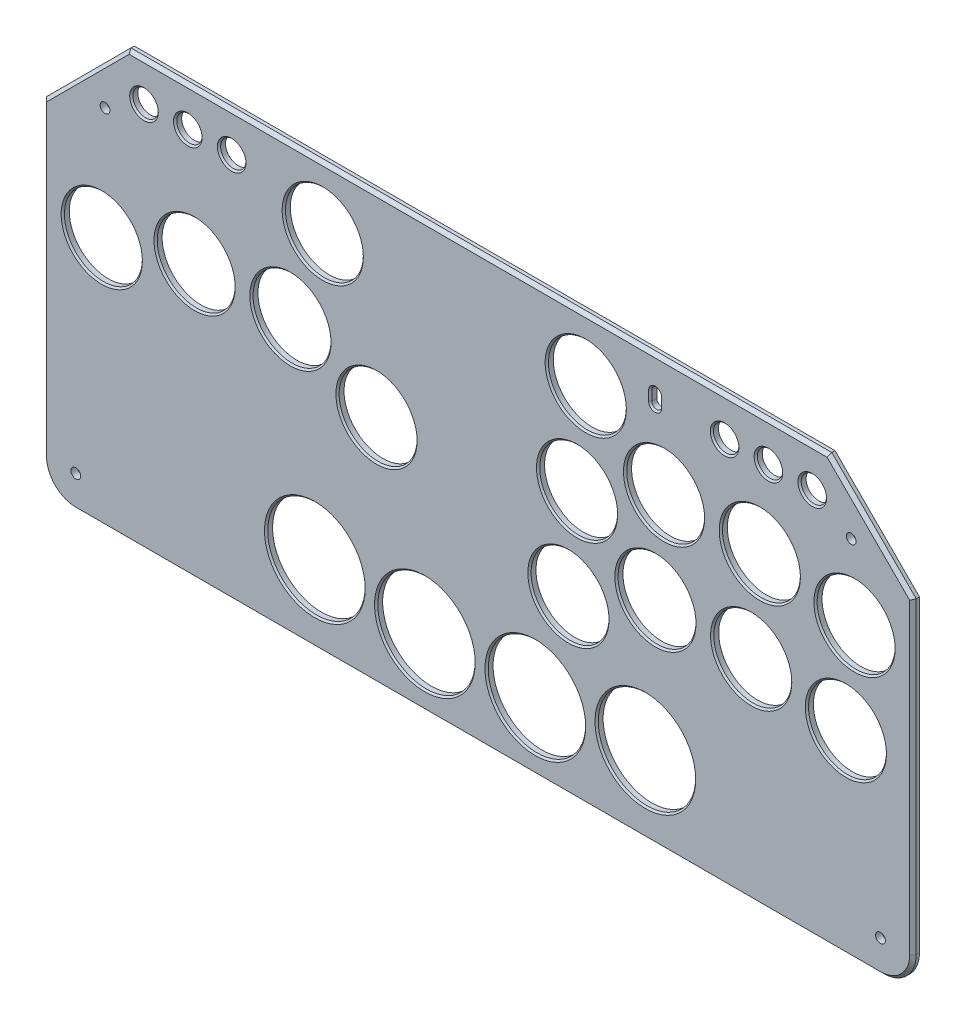
SolidWorks part; units mm, degrees
ref_plane "Front Plane" through (0, 0, 0) normal (0, 0, 1) x (1, 0, 0)
ref_plane "Top Plane" through (0, 0, 0) normal (0, 1, 0) x (1, 0, 0)
ref_plane "Right Plane" through (0, 0, 0) normal (1, 0, 0) x (0, 0, -1)
sketch "Sketch1" plane through (0, 0, 0) normal (0, 0, 1) x (1, 0, 0)
  line L0 (157.8919, 26.2701) -> (191.7747, 29.0915)
  line L1 (157.8919, 26.2701) -> (191.7747, 26.2701)
  line L2 (157.8919, 26.2701) -> (157.8919, 29.0915)
  line L3 (157.8919, 29.0915) -> (191.7747, 29.0915)
  line L4 (191.7747, 26.2701) -> (191.7747, 29.0915)
  line L5 (123.8919, 26.2701) -> (90.0092, 26.2701)
  line L6 (123.8919, 26.2701) -> (123.8919, 29.0915)
  line L7 (123.8919, 29.0915) -> (90.0092, 29.0915)
  line L8 (90.0092, 26.2701) -> (90.0092, 29.0915)
  line L9 (90.0092, 29.0915) -> (123.8919, 26.2701)
  line L10 (168.0919, 58.3601) -> (194.8735, 70.7292)
  line L11 (168.0919, 58.3601) -> (194.8735, 58.3601)
  line L12 (168.0919, 58.3601) -> (168.0919, 70.7292)
  line L13 (168.0919, 70.7292) -> (194.8735, 70.7292)
  line L14 (194.8735, 58.3601) -> (194.8735, 70.7292)
  line L15 (194.8735, 70.7292) -> (224.3587, 70.7292)
  line L16 (194.8735, 70.7292) -> (194.8735, 69.7923)
  line L17 (194.8735, 69.7923) -> (224.3587, 69.7923)
  line L18 (224.3587, 70.7292) -> (224.3587, 69.7923)
  line L19 (224.3587, 69.7923) -> (253.5106, 69.7923)
  line L20 (224.3587, 69.7923) -> (224.3587, 65.2742)
  line L21 (224.3587, 65.2742) -> (253.5106, 65.2742)
  line L22 (253.5106, 69.7923) -> (253.5106, 65.2742)
  line L23 (224.3587, 69.7923) -> (194.8735, 70.7292)
  line L24 (253.5106, 65.2742) -> (224.3587, 69.7923)
  line L25 (170.7502, 87.7401) -> (168.0919, 58.3601)
  line L26 (168.0919, 58.3601) -> (170.7502, 58.3601)
  line L27 (168.0919, 58.3601) -> (168.0919, 87.7401)
  line L28 (168.0919, 87.7401) -> (170.7502, 87.7401)
  line L29 (170.7502, 58.3601) -> (170.7502, 87.7401)
  line L30 (52.9966, 89.4705) -> (24.4119, 82.1791)
  line L31 (24.4119, 82.1791) -> (52.9966, 82.1791)
  line L32 (24.4119, 82.1791) -> (24.4119, 89.4705)
  line L33 (24.4119, 89.4705) -> (52.9966, 89.4705)
  line L34 (52.9966, 82.1791) -> (52.9966, 89.4705)
  line L35 (82.4966, 89.4705) -> (109.0019, 89.4705)
  line L36 (82.4966, 89.4705) -> (82.4966, 76.5201)
  line L37 (82.4966, 76.5201) -> (109.0019, 76.5201)
  line L38 (109.0019, 89.4705) -> (109.0019, 76.5201)
  line L39 (92.4554, 117.2387) -> (82.4966, 117.2387)
  line L40 (92.4554, 117.2387) -> (92.4554, 89.4705)
  line L41 (92.4554, 89.4705) -> (82.4966, 89.4705)
  line L42 (82.4966, 117.2387) -> (82.4966, 89.4705)
  line L43 (92.4554, 117.2387) -> (82.4966, 89.4705)
  line L44 (109.0019, 76.5201) -> (82.4966, 89.4705)
  circle A0 centre (123.8919, 26.2701) radius 14.25
  circle A1 centre (157.8919, 26.2701) radius 14.25
  circle A2 centre (90.0092, 29.0915) radius 14.25
  circle A3 centre (191.7747, 29.0915) radius 14.25
  circle A4 centre (82.4966, 89.4705) radius 11.25
  circle A5 centre (92.4554, 117.2387) radius 11.25
  circle A6 centre (52.9966, 89.4705) radius 11.25
  circle A7 centre (109.0019, 76.5201) radius 11.25
  circle A8 centre (24.4119, 82.1791) radius 11.25
  circle A9 centre (170.7502, 87.7401) radius 11.25
  circle A10 centre (168.0919, 58.3601) radius 11.25
  circle A11 centre (197.5318, 100.1092) radius 11.25
  circle A12 centre (194.8735, 70.7292) radius 11.25
  circle A13 centre (227.0169, 99.1723) radius 11.25
  circle A14 centre (224.3587, 69.7923) radius 11.25
  circle A15 centre (256.1689, 94.6541) radius 11.25
  circle A16 centre (253.5106, 65.2742) radius 11.25
  circle A17 centre (24.4119, 82.1791) radius 12
  circle A18 centre (52.9966, 89.4705) radius 12
  circle A19 centre (92.4554, 117.2387) radius 12
  circle A20 centre (82.4966, 89.4705) radius 12
  circle A21 centre (109.0019, 76.5201) radius 12
  circle A22 centre (168.0919, 58.3601) radius 12
  circle A23 centre (194.8735, 70.7292) radius 12
  circle A24 centre (224.3587, 69.7923) radius 12
  circle A25 centre (253.5106, 65.2742) radius 12
  circle A26 centre (256.1689, 94.6541) radius 12
  circle A27 centre (227.0169, 99.1723) radius 12
  circle A28 centre (197.5318, 100.1092) radius 12
  circle A29 centre (170.7502, 87.7401) radius 12
  circle A30 centre (191.7747, 29.0915) radius 15
  circle A31 centre (157.8919, 26.2701) radius 15
  circle A32 centre (123.8919, 26.2701) radius 15
  circle A33 centre (90.0092, 29.0915) radius 15
  circle A34 centre (173.429, 117.1182) radius 11.25
  circle A35 centre (173.429, 117.1182) radius 12
  dimension "D1" = 28.5
  dimension "D2" = 22.5
  dimension "D3" = 0.75
  dimension "D4" = 0.75
  dimension "D34" = 34
  dimension "D5" = 29.5
  dimension "D6" = 29.5
  dimension "D7" = 29.5
  dimension "D8" = 29.5
  dimension "D9" = 29.5
  dimension "D10" = 29.5
  dimension "D11" = 29.5
  dimension "D12" = 29.5
  dimension "D13" = 29.5
  dimension "D14" = 29.5
  dimension "D15" = 29.5
  dimension "D16" = 29.5
  dimension "D17" = 29.5
  dimension "D18" = 29.5
  dimension "D19" = 34
  dimension "D20" = 34
  dimension "D21" = 32.09
  dimension "D22" = 10.2
  dimension "D23" = 4.76
  dimension "D24" = 4.76
  dimension "D25" = 24.79
  dimension "D26" = 1.82
  dimension "D27" = 8.81
  dimension "D28" = 84.83
  dimension "D29" = 75.69
  dimension "D30" = 70.27
  dimension "D31" = 26.04
  dimension "D32" = 14.89
  dimension "D33" = 50.25
  dimension "D35" = 29.5
  dimension "D36" = 29.5
sketch "Sketch4" plane through (-30.2083, 20.075, 0) normal (0, 0, 1) x (0.9781, -0.2079, 0)
  line L0 (86.1706, 94.1917) -> (105.2206, 75.1417)
  line L1 (67.1206, 94.1917) -> (86.1706, 94.1917)
  line L2 (67.1206, 94.1917) -> (67.1206, 75.1417)
  line L3 (67.1206, 75.1417) -> (86.1706, 75.1417)
  line L4 (86.1706, 94.1917) -> (86.1706, 75.1417)
  line L5 (86.1706, 94.1917) -> (105.2206, 94.1917)
  line L6 (86.1706, 94.1917) -> (86.1706, 75.1417)
  line L7 (86.1706, 75.1417) -> (105.2206, 75.1417)
  line L8 (105.2206, 94.1917) -> (105.2206, 75.1417)
  line L9 (105.2206, 94.1917) -> (124.2706, 94.1917)
  line L10 (105.2206, 94.1917) -> (105.2206, 75.1417)
  line L11 (105.2206, 75.1417) -> (124.2706, 75.1417)
  line L12 (124.2706, 94.1917) -> (124.2706, 75.1417)
  line L13 (86.1706, 94.1917) -> (105.2206, 94.1917)
  line L14 (86.1706, 94.1917) -> (86.1706, 113.2417)
  line L15 (86.1706, 113.2417) -> (105.2206, 113.2417)
  line L16 (105.2206, 94.1917) -> (105.2206, 113.2417)
  line L17 (66.9585, 85.1784) -> (124.4326, 84.1551)
  point P14 (95.6956, 84.6667)
  point P15 (95.6956, 84.6667)
  dimension "D1" = 19.05
sketch "Sketch9" plane through (0, 0, 0) normal (0, 0, 1) x (1, 0, 0)
  line L1 (17.3619, 89.2291) -> (31.4619, 89.2291)
  line L2 (17.3619, 89.2291) -> (17.3619, 75.1291)
  line L3 (17.3619, 75.1291) -> (31.4619, 75.1291)
  line L4 (31.4619, 89.2291) -> (31.4619, 75.1291)
  line L5 (45.9466, 96.5205) -> (60.0466, 96.5205)
  line L6 (45.9466, 96.5205) -> (45.9466, 82.4205)
  line L7 (45.9466, 82.4205) -> (60.0466, 82.4205)
  line L8 (60.0466, 96.5205) -> (60.0466, 82.4205)
  line L9 (75.4466, 96.5205) -> (89.5466, 96.5205)
  line L10 (75.4466, 96.5205) -> (75.4466, 82.4205)
  line L11 (75.4466, 82.4205) -> (89.5466, 82.4205)
  line L12 (89.5466, 96.5205) -> (89.5466, 82.4205)
  line L13 (101.9519, 83.5701) -> (116.0519, 83.5701)
  line L14 (101.9519, 83.5701) -> (101.9519, 69.4701)
  line L15 (101.9519, 69.4701) -> (116.0519, 69.4701)
  line L16 (116.0519, 83.5701) -> (116.0519, 69.4701)
  line L17 (85.4054, 124.2887) -> (99.5054, 124.2887)
  line L18 (85.4054, 124.2887) -> (85.4054, 110.1887)
  line L19 (85.4054, 110.1887) -> (99.5054, 110.1887)
  line L20 (99.5054, 124.2887) -> (99.5054, 110.1887)
  line L21 (82.9592, 36.1415) -> (97.0592, 36.1415)
  line L22 (82.9592, 36.1415) -> (82.9592, 22.0415)
  line L23 (82.9592, 22.0415) -> (97.0592, 22.0415)
  line L24 (97.0592, 36.1415) -> (97.0592, 22.0415)
  line L25 (116.8419, 33.3201) -> (130.9419, 33.3201)
  line L26 (116.8419, 33.3201) -> (116.8419, 19.2201)
  line L27 (116.8419, 19.2201) -> (130.9419, 19.2201)
  line L28 (130.9419, 33.3201) -> (130.9419, 19.2201)
  line L29 (150.8419, 33.3201) -> (164.9419, 33.3201)
  line L30 (150.8419, 33.3201) -> (150.8419, 19.2201)
  line L31 (150.8419, 19.2201) -> (164.9419, 19.2201)
  line L32 (164.9419, 33.3201) -> (164.9419, 19.2201)
  line L33 (184.7247, 36.1415) -> (198.8247, 36.1415)
  line L34 (184.7247, 36.1415) -> (184.7247, 22.0415)
  line L35 (184.7247, 22.0415) -> (198.8247, 22.0415)
  line L36 (198.8247, 36.1415) -> (198.8247, 22.0415)
  line L37 (260.5606, 58.2242) -> (246.4606, 58.2242)
  line L38 (260.5606, 58.2242) -> (260.5606, 72.3242)
  line L39 (260.5606, 72.3242) -> (246.4606, 72.3242)
  line L40 (246.4606, 58.2242) -> (246.4606, 72.3242)
  line L41 (217.3087, 76.8423) -> (231.4087, 76.8423)
  line L42 (217.3087, 76.8423) -> (217.3087, 62.7423)
  line L43 (217.3087, 62.7423) -> (231.4087, 62.7423)
  line L44 (231.4087, 76.8423) -> (231.4087, 62.7423)
  line L45 (187.8235, 77.7792) -> (201.9235, 77.7792)
  line L46 (187.8235, 77.7792) -> (187.8235, 63.6792)
  line L47 (187.8235, 63.6792) -> (201.9235, 63.6792)
  line L48 (201.9235, 77.7792) -> (201.9235, 63.6792)
  line L49 (161.0419, 65.4101) -> (175.1419, 65.4101)
  line L50 (161.0419, 65.4101) -> (161.0419, 51.3101)
  line L51 (161.0419, 51.3101) -> (175.1419, 51.3101)
  line L52 (175.1419, 65.4101) -> (175.1419, 51.3101)
  line L53 (163.7002, 94.7901) -> (177.8002, 94.7901)
  line L54 (163.7002, 94.7901) -> (163.7002, 80.6901)
  line L55 (163.7002, 80.6901) -> (177.8002, 80.6901)
  line L56 (177.8002, 94.7901) -> (177.8002, 80.6901)
  line L57 (190.4818, 107.1592) -> (204.5818, 107.1592)
  line L58 (190.4818, 107.1592) -> (190.4818, 93.0592)
  line L59 (190.4818, 93.0592) -> (204.5818, 93.0592)
  line L60 (204.5818, 107.1592) -> (204.5818, 93.0592)
  line L61 (219.9669, 106.2223) -> (234.0669, 106.2223)
  line L62 (219.9669, 106.2223) -> (219.9669, 92.1223)
  line L63 (219.9669, 92.1223) -> (234.0669, 92.1223)
  line L64 (234.0669, 106.2223) -> (234.0669, 92.1223)
  line L65 (249.1189, 101.7041) -> (263.2189, 101.7041)
  line L66 (249.1189, 101.7041) -> (249.1189, 87.6041)
  line L67 (249.1189, 87.6041) -> (263.2189, 87.6041)
  line L68 (263.2189, 101.7041) -> (263.2189, 87.6041)
  line L69 (166.379, 124.1682) -> (180.479, 124.1682)
  line L70 (166.379, 124.1682) -> (166.379, 110.0682)
  line L71 (166.379, 110.0682) -> (180.479, 110.0682)
  line L72 (180.479, 124.1682) -> (180.479, 110.0682)
  point P72 (24.4119, 89.2291)
  point P74 (52.9966, 96.5205)
  point P76 (82.4966, 96.5205)
  point P78 (92.4554, 124.2887)
  point P80 (109.0019, 83.5701)
  point P82 (90.0092, 36.1415)
  point P84 (123.8919, 33.3201)
  point P86 (157.8919, 33.3201)
  point P88 (191.7747, 36.1415)
  point P90 (168.0919, 65.4101)
  point P92 (170.7502, 94.7901)
  point P94 (173.429, 124.1682)
  point P96 (197.5318, 107.1592)
  point P98 (227.0169, 106.2223)
  point P100 (256.1689, 101.7041)
  point P102 (194.8735, 77.7792)
  point P104 (224.3587, 76.8423)
  point P106 (253.5106, 72.3242)
  point P108 (17.3619, 82.1791)
  point P109 (45.9466, 89.4705)
  point P110 (75.4466, 89.4705)
  point P111 (101.9519, 76.5201)
  point P112 (85.4054, 117.2387)
  point P113 (82.9592, 29.0915)
  point P114 (116.8419, 26.2701)
  point P115 (150.8419, 26.2701)
  point P116 (184.7247, 29.0915)
  point P118 (161.0419, 58.3601)
  point P119 (187.8235, 70.7292)
  point P120 (217.3087, 69.7923)
  point P121 (246.4606, 65.2742)
  point P122 (163.7002, 87.7401)
  point P123 (190.4818, 100.1092)
  point P124 (219.9669, 99.1723)
  point P125 (249.1189, 94.6541)
  point P126 (166.379, 117.1182)
  dimension "D1" = 14.1
sketch "Sketch10" plane through (-22.0981, 19.3454, 0) normal (0, 0, 1) x (0.9781, -0.2079, 0)
  line L1 (61.5108, 90.7441) -> (75.6108, 90.7441)
  line L2 (61.5108, 90.7441) -> (61.5108, 76.6441)
  line L3 (61.5108, 76.6441) -> (75.6108, 76.6441)
  line L4 (75.6108, 90.7441) -> (75.6108, 76.6441)
  line L5 (80.5608, 90.7441) -> (94.6608, 90.7441)
  line L6 (80.5608, 90.7441) -> (80.5608, 76.6441)
  line L7 (80.5608, 76.6441) -> (94.6608, 76.6441)
  line L8 (94.6608, 90.7441) -> (94.6608, 76.6441)
  line L9 (99.6108, 90.7441) -> (113.7108, 90.7441)
  line L10 (99.6108, 90.7441) -> (99.6108, 76.6441)
  line L11 (99.6108, 76.6441) -> (113.7108, 76.6441)
  line L12 (113.7108, 90.7441) -> (113.7108, 76.6441)
  line L13 (80.5608, 109.7941) -> (94.6608, 109.7941)
  line L14 (80.5608, 109.7941) -> (80.5608, 95.6941)
  line L15 (80.5608, 95.6941) -> (94.6608, 95.6941)
  line L16 (94.6608, 109.7941) -> (94.6608, 95.6941)
  line L17 (50.5121, 89.6359) -> (53.4436, 75.8441) construction
  line L18 (59.0358, 93.2191) -> (78.0858, 93.2191) construction
  line L19 (78.0858, 112.2691) -> (97.1358, 112.2691) construction
  line L20 (97.1358, 93.2191) -> (116.1858, 93.2191) construction
  line L21 (78.0858, 93.2191) -> (78.0858, 112.2691) construction
  line L23 (59.0358, 93.2191) -> (59.0358, 74.1691) construction
  point P16 (75.6108, 83.6941)
  point P17 (94.6608, 83.6941)
  point P18 (113.7108, 83.6941)
  point P19 (87.6108, 90.7441)
  point P20 (87.6108, 109.7941)
  point P23 (68.5608, 90.7441)
  point P26 (68.5608, 93.2191)
  point P29 (87.6108, 112.2691)
  point P30 (106.6608, 90.7441)
  point P33 (106.6608, 93.2191)
  point P34 (80.5608, 102.7441)
  point P37 (78.0858, 102.7441)
  point P42 (59.0358, 83.6941)
  point P43 (61.5108, 83.6941)
sketch "Sketch14" plane through (0, 0, 0) normal (0, 0, 1) x (1, 0, 0)
  line L0 (165.1144, 80.6901) -> (163.7002, 82.1043)
  line L1 (163.7002, 93.3758) -> (165.1144, 94.7901)
  line L2 (177.8002, 93.3758) -> (176.386, 94.7901)
  line L3 (179.0648, 110.0682) -> (180.479, 111.4824)
  line L4 (166.379, 111.4824) -> (167.7932, 110.0682)
  line L5 (166.379, 122.754) -> (167.7932, 124.1682)
  line L6 (179.0648, 124.1682) -> (180.479, 122.754)
  line L7 (203.1676, 93.0592) -> (204.5818, 94.4734)
  line L8 (17.3619, 89.2291) -> (17.3619, 75.1291) construction
  line L9 (17.3619, 89.2291) -> (31.4619, 89.2291) construction
  line L10 (17.3619, 87.8149) -> (18.7761, 89.2291)
  line L11 (17.3619, 75.1291) -> (31.4619, 75.1291) construction
  line L12 (31.4619, 89.2291) -> (31.4619, 75.1291) construction
  line L13 (45.9466, 96.5205) -> (60.0466, 96.5205) construction
  line L14 (60.0466, 96.5205) -> (60.0466, 82.4205) construction
  line L15 (45.9466, 96.5205) -> (45.9466, 82.4205) construction
  line L16 (45.9466, 82.4205) -> (60.0466, 82.4205) construction
  line L17 (85.4054, 124.2887) -> (85.4054, 110.1887) construction
  line L18 (85.4054, 124.2887) -> (99.5054, 124.2887) construction
  line L19 (99.5054, 124.2887) -> (99.5054, 110.1887) construction
  line L20 (85.4054, 110.1887) -> (99.5054, 110.1887) construction
  line L21 (101.9519, 83.5701) -> (101.9519, 69.4701) construction
  line L22 (101.9519, 83.5701) -> (116.0519, 83.5701) construction
  line L23 (116.0519, 83.5701) -> (116.0519, 69.4701) construction
  line L24 (101.9519, 69.4701) -> (116.0519, 69.4701) construction
  line L25 (91.2712, 73.6044) -> (105.0631, 70.6729) construction
  line L26 (107.9947, 84.4647) -> (105.0631, 70.6729) construction
  line L27 (94.2028, 87.3963) -> (107.9947, 84.4647) construction
  line L28 (94.2028, 87.3963) -> (91.2712, 73.6044) construction
  line L29 (72.6375, 77.5651) -> (86.4294, 74.6336) construction
  line L30 (89.361, 88.4255) -> (86.4294, 74.6336) construction
  line L31 (75.5691, 91.357) -> (89.361, 88.4255) construction
  line L32 (75.5691, 91.357) -> (72.6375, 77.5651) construction
  line L33 (56.9354, 95.3177) -> (54.0038, 81.5259) construction
  line L34 (56.9354, 95.3177) -> (70.7273, 92.3862) construction
  line L35 (70.7273, 92.3862) -> (67.7957, 78.5943) construction
  line L36 (54.0038, 81.5259) -> (67.7957, 78.5943) construction
  line L37 (76.5983, 96.1988) -> (90.3901, 93.2673) construction
  line L38 (93.3217, 107.0592) -> (90.3901, 93.2673) construction
  line L39 (79.5298, 109.9907) -> (76.5983, 96.1988) construction
  line L40 (79.5298, 109.9907) -> (93.3217, 107.0592) construction
  line L41 (82.9592, 36.1415) -> (82.9592, 22.0415) construction
  line L42 (82.9592, 36.1415) -> (97.0592, 36.1415) construction
  line L43 (82.9592, 22.0415) -> (97.0592, 22.0415) construction
  line L44 (97.0592, 36.1415) -> (97.0592, 22.0415) construction
  line L45 (116.8419, 33.3201) -> (116.8419, 19.2201) construction
  line L46 (116.8419, 33.3201) -> (130.9419, 33.3201) construction
  line L47 (116.8419, 19.2201) -> (130.9419, 19.2201) construction
  line L48 (130.9419, 33.3201) -> (130.9419, 19.2201) construction
  line L49 (150.8419, 33.3201) -> (150.8419, 19.2201) construction
  line L50 (150.8419, 33.3201) -> (164.9419, 33.3201) construction
  line L51 (164.9419, 33.3201) -> (164.9419, 19.2201) construction
  line L52 (150.8419, 19.2201) -> (164.9419, 19.2201) construction
  line L53 (184.7247, 36.1415) -> (184.7247, 22.0415) construction
  line L54 (184.7247, 22.0415) -> (198.8247, 22.0415) construction
  line L55 (198.8247, 36.1415) -> (198.8247, 22.0415) construction
  line L56 (184.7247, 36.1415) -> (198.8247, 36.1415) construction
  line L57 (161.0419, 65.4101) -> (175.1419, 65.4101) construction
  line L58 (175.1419, 65.4101) -> (175.1419, 51.3101) construction
  line L59 (161.0419, 51.3101) -> (175.1419, 51.3101) construction
  line L60 (161.0419, 65.4101) -> (161.0419, 51.3101) construction
  line L61 (187.8235, 77.7792) -> (187.8235, 63.6792) construction
  line L62 (187.8235, 77.7792) -> (201.9235, 77.7792) construction
  line L63 (187.8235, 63.6792) -> (201.9235, 63.6792) construction
  line L64 (201.9235, 77.7792) -> (201.9235, 63.6792) construction
  line L65 (217.3087, 76.8423) -> (217.3087, 62.7423) construction
  line L66 (217.3087, 76.8423) -> (231.4087, 76.8423) construction
  line L67 (231.4087, 76.8423) -> (231.4087, 62.7423) construction
  line L68 (217.3087, 62.7423) -> (231.4087, 62.7423) construction
  line L69 (260.5606, 58.2242) -> (246.4606, 58.2242) construction
  line L70 (260.5606, 58.2242) -> (260.5606, 72.3242) construction
  line L71 (246.4606, 58.2242) -> (246.4606, 72.3242) construction
  line L72 (260.5606, 72.3242) -> (246.4606, 72.3242) construction
  line L73 (249.1189, 101.7041) -> (263.2189, 101.7041) construction
  line L74 (263.2189, 101.7041) -> (263.2189, 87.6041) construction
  line L75 (249.1189, 87.6041) -> (263.2189, 87.6041) construction
  line L76 (249.1189, 101.7041) -> (249.1189, 87.6041) construction
  line L77 (219.9669, 106.2223) -> (219.9669, 92.1223) construction
  line L78 (219.9669, 106.2223) -> (234.0669, 106.2223) construction
  line L79 (234.0669, 106.2223) -> (234.0669, 92.1223) construction
  line L80 (219.9669, 92.1223) -> (234.0669, 92.1223) construction
  line L81 (190.4818, 107.1592) -> (204.5818, 107.1592) construction
  line L82 (204.5818, 107.1592) -> (204.5818, 93.0592) construction
  line L83 (190.4818, 93.0592) -> (204.5818, 93.0592) construction
  line L84 (190.4818, 107.1592) -> (190.4818, 93.0592) construction
  line L85 (163.7002, 94.7901) -> (177.8002, 94.7901) construction
  line L86 (177.8002, 94.7901) -> (177.8002, 80.6901) construction
  line L87 (163.7002, 80.6901) -> (177.8002, 80.6901) construction
  line L88 (163.7002, 94.7901) -> (163.7002, 80.6901) construction
  line L89 (180.479, 124.1682) -> (180.479, 110.0682) construction
  line L90 (166.379, 110.0682) -> (180.479, 110.0682) construction
  line L91 (166.379, 124.1682) -> (166.379, 110.0682) construction
  line L92 (166.379, 124.1682) -> (180.479, 124.1682) construction
  line L93 (17.3619, 76.5433) -> (18.7761, 75.1291)
  line L94 (30.0477, 75.1291) -> (31.4619, 76.5433)
  line L95 (31.4619, 87.8149) -> (30.0477, 89.2291)
  line L96 (45.9466, 95.1063) -> (47.3608, 96.5205)
  line L97 (45.9466, 83.8347) -> (47.3608, 82.4205)
  line L98 (54.2979, 82.9092) -> (55.3871, 81.2318)
  line L99 (58.6323, 82.4205) -> (60.0466, 83.8347)
  line L100 (56.6413, 93.9344) -> (58.3187, 95.0237)
  line L101 (58.6323, 96.5205) -> (60.0466, 95.1063)
  line L102 (69.3439, 92.6802) -> (70.4332, 91.0029)
  line L103 (68.0897, 79.9776) -> (66.4124, 78.8883)
  line L104 (75.2751, 89.9737) -> (76.9524, 91.063)
  line L105 (72.9316, 78.9484) -> (74.0208, 77.2711)
  line L106 (85.0461, 74.9276) -> (86.7234, 76.0169)
  line L107 (89.0669, 87.0421) -> (87.9777, 88.7195)
  line L108 (89.0068, 93.5613) -> (90.6842, 94.6506)
  line L109 (76.8923, 97.5822) -> (77.9816, 95.9048)
  line L110 (91.9384, 107.3532) -> (93.0277, 105.6759)
  line L111 (79.2358, 108.6074) -> (80.9131, 109.6967)
  line L112 (85.4054, 111.6029) -> (86.8196, 110.1887)
  line L113 (98.0912, 110.1887) -> (99.5054, 111.6029)
  line L114 (98.0912, 124.2887) -> (99.5054, 122.8745)
  line L115 (85.4054, 122.8745) -> (86.8196, 124.2887)
  line L116 (93.9088, 86.013) -> (95.5861, 87.1023)
  line L117 (91.5653, 74.9877) -> (92.6546, 73.3104)
  line L118 (103.6798, 70.9669) -> (105.3572, 72.0562)
  line L119 (106.6114, 84.7588) -> (107.7006, 83.0814)
  line L120 (101.9519, 82.1559) -> (103.3662, 83.5701)
  line L121 (101.9519, 70.8843) -> (103.3662, 69.4701)
  line L122 (114.6377, 69.4701) -> (116.0519, 70.8843)
  line L123 (116.0519, 82.1559) -> (114.6377, 83.5701)
  line L124 (82.9592, 34.7272) -> (84.3734, 36.1415)
  line L125 (82.9592, 23.4557) -> (84.3734, 22.0415)
  line L126 (95.645, 22.0415) -> (97.0592, 23.4557)
  line L127 (97.0592, 34.7272) -> (95.645, 36.1415)
  line L128 (116.8419, 31.9059) -> (118.2562, 33.3201)
  line L129 (116.8419, 20.6343) -> (118.2562, 19.2201)
  line L130 (129.5277, 19.2201) -> (130.9419, 20.6343)
  line L131 (130.9419, 31.9059) -> (129.5277, 33.3201)
  line L132 (150.8419, 31.9059) -> (152.2562, 33.3201)
  line L133 (150.8419, 20.6343) -> (152.2562, 19.2201)
  line L134 (163.5277, 19.2201) -> (164.9419, 20.6343)
  line L135 (164.9419, 31.9059) -> (163.5277, 33.3201)
  line L136 (184.7247, 34.7272) -> (186.1389, 36.1415)
  line L137 (184.7247, 23.4557) -> (186.1389, 22.0415)
  line L138 (197.4105, 22.0415) -> (198.8247, 23.4557)
  line L139 (198.8247, 34.7272) -> (197.4105, 36.1415)
  line L140 (173.7277, 51.3101) -> (175.1419, 52.7243)
  line L141 (161.0419, 52.7243) -> (162.4562, 51.3101)
  line L142 (161.0419, 63.9959) -> (162.4562, 65.4101)
  line L143 (173.7277, 65.4101) -> (175.1419, 63.9959)
  line L144 (187.8235, 65.0934) -> (189.2378, 63.6792)
  line L145 (200.5093, 63.6792) -> (201.9235, 65.0934)
  line L146 (200.5093, 77.7792) -> (201.9235, 76.365)
  line L147 (187.8235, 76.365) -> (189.2378, 77.7792)
  line L148 (176.386, 80.6901) -> (177.8002, 82.1043)
  line L149 (204.5818, 105.745) -> (203.1676, 107.1592)
  line L150 (191.896, 107.1592) -> (190.4818, 105.745)
  line L151 (190.4818, 94.4734) -> (191.896, 93.0592)
  line L152 (219.9669, 104.8081) -> (221.3812, 106.2223)
  line L153 (232.6527, 106.2223) -> (234.0669, 104.8081)
  line L154 (234.0669, 93.5365) -> (232.6527, 92.1223)
  line L155 (219.9669, 93.5365) -> (221.3812, 92.1223)
  line L156 (229.9944, 76.8423) -> (231.4087, 75.4281)
  line L157 (217.3087, 75.4281) -> (218.7229, 76.8423)
  line L158 (217.3087, 64.1565) -> (218.7229, 62.7423)
  line L159 (229.9944, 62.7423) -> (231.4087, 64.1565)
  line L160 (259.1464, 72.3242) -> (260.5606, 70.9099)
  line L161 (246.4606, 70.9099) -> (247.8748, 72.3242)
  line L162 (259.1464, 58.2242) -> (260.5606, 59.6384)
  line L163 (247.8748, 58.2242) -> (246.4606, 59.6384)
  line L164 (261.8047, 87.6041) -> (263.2189, 89.0183)
  line L165 (249.1189, 89.0183) -> (250.5331, 87.6041)
  line L166 (249.1189, 100.2899) -> (250.5331, 101.7041)
  line L167 (261.8047, 101.7041) -> (263.2189, 100.2899)
  line L168 (75.4466, 96.5205) -> (75.4466, 82.4205) construction
  line L169 (75.4466, 96.5205) -> (89.5466, 96.5205) construction
  line L170 (89.5466, 96.5205) -> (89.5466, 82.4205) construction
  line L171 (75.4466, 82.4205) -> (89.5466, 82.4205) construction
  line L172 (76.8608, 96.5205) -> (75.4466, 95.1063)
  line L173 (88.1323, 96.5205) -> (89.5466, 95.1063)
  line L174 (89.5466, 83.8347) -> (88.1323, 82.4205)
  line L175 (75.4466, 83.8347) -> (76.8608, 82.4205)
  arc A0 (17.3619, 87.8149) -> (18.7761, 89.2291) centre (18.069, 88.522) cw
  arc A1 (18.7761, 75.1291) -> (17.3619, 76.5433) centre (18.069, 75.8362) cw
  arc A2 (31.4619, 76.5433) -> (30.0477, 75.1291) centre (30.7548, 75.8362) cw
  arc A3 (30.0477, 89.2291) -> (31.4619, 87.8149) centre (30.7548, 88.522) cw
  arc A4 (58.6323, 96.5205) -> (60.0466, 95.1063) centre (59.3394, 95.8134) cw
  arc A5 (45.9466, 95.1063) -> (47.3608, 96.5205) centre (46.6537, 95.8134) cw
  arc A6 (47.3608, 82.4205) -> (45.9466, 83.8347) centre (46.6537, 83.1276) cw
  arc A7 (60.0466, 83.8347) -> (58.6323, 82.4205) centre (59.3394, 83.1276) cw
  arc A8 (85.4054, 122.8745) -> (86.8196, 124.2887) centre (86.1125, 123.5816) cw
  arc A9 (98.0912, 124.2887) -> (99.5054, 122.8745) centre (98.7983, 123.5816) cw
  arc A10 (99.5054, 111.6029) -> (98.0912, 110.1887) centre (98.7983, 110.8958) cw
  arc A11 (85.4054, 111.6029) -> (86.8196, 110.1887) centre (86.1125, 110.8958) ccw
  arc A12 (101.9519, 82.1559) -> (103.3662, 83.5701) centre (102.6591, 82.863) cw
  arc A13 (114.6377, 83.5701) -> (116.0519, 82.1559) centre (115.3448, 82.863) cw
  arc A14 (116.0519, 70.8843) -> (114.6377, 69.4701) centre (115.3448, 70.1772) cw
  arc A15 (101.9519, 70.8843) -> (103.3662, 69.4701) centre (102.6591, 70.1772) ccw
  arc A16 (103.6798, 70.9669) -> (105.3572, 72.0562) centre (104.5185, 71.5115) ccw
  arc A17 (106.6114, 84.7588) -> (107.7006, 83.0814) centre (107.156, 83.9201) cw
  arc A18 (93.9088, 86.013) -> (95.5861, 87.1023) centre (94.7474, 86.5576) cw
  arc A19 (91.5653, 74.9877) -> (92.6546, 73.3104) centre (92.1099, 74.1491) ccw
  arc A20 (85.0461, 74.9276) -> (86.7234, 76.0169) centre (85.8848, 75.4722) ccw
  arc A21 (87.9777, 88.7195) -> (89.0669, 87.0421) centre (88.5223, 87.8808) cw
  arc A22 (75.2751, 89.9737) -> (76.9524, 91.063) centre (76.1137, 90.5183) cw
  arc A23 (72.9316, 78.9484) -> (74.0208, 77.2711) centre (73.4762, 78.1098) ccw
  arc A24 (56.6413, 93.9344) -> (58.3187, 95.0237) centre (57.48, 94.4791) cw
  arc A25 (69.3439, 92.6802) -> (70.4332, 91.0029) centre (69.8886, 91.8415) cw
  arc A26 (68.0897, 79.9776) -> (66.4124, 78.8883) centre (67.2511, 79.433) cw
  arc A27 (54.2979, 82.9092) -> (55.3871, 81.2318) centre (54.8425, 82.0705) ccw
  arc A28 (89.0068, 93.5613) -> (90.6842, 94.6506) centre (89.8455, 94.106) ccw
  arc A29 (76.8923, 97.5822) -> (77.9816, 95.9048) centre (77.4369, 96.7435) ccw
  arc A30 (79.2358, 108.6074) -> (80.9131, 109.6967) centre (80.0744, 109.1521) cw
  arc A31 (91.9384, 107.3532) -> (93.0277, 105.6759) centre (92.483, 106.5145) cw
  arc A32 (82.9592, 34.7272) -> (84.3734, 36.1415) centre (83.6663, 35.4344) cw
  arc A33 (82.9592, 23.4557) -> (84.3734, 22.0415) centre (83.6663, 22.7486) ccw
  arc A34 (95.645, 22.0415) -> (97.0592, 23.4557) centre (96.3521, 22.7486) ccw
  arc A35 (95.645, 36.1415) -> (97.0592, 34.7272) centre (96.3521, 35.4344) cw
  arc A36 (116.8419, 31.9059) -> (118.2562, 33.3201) centre (117.5491, 32.613) cw
  arc A37 (116.8419, 20.6343) -> (118.2562, 19.2201) centre (117.5491, 19.9272) ccw
  arc A38 (129.5277, 19.2201) -> (130.9419, 20.6343) centre (130.2348, 19.9272) ccw
  arc A39 (129.5277, 33.3201) -> (130.9419, 31.9059) centre (130.2348, 32.613) cw
  arc A40 (150.8419, 31.9059) -> (152.2562, 33.3201) centre (151.5491, 32.613) cw
  arc A41 (163.5277, 33.3201) -> (164.9419, 31.9059) centre (164.2348, 32.613) cw
  arc A42 (164.9419, 20.6343) -> (163.5277, 19.2201) centre (164.2348, 19.9272) cw
  arc A43 (150.8419, 20.6343) -> (152.2562, 19.2201) centre (151.5491, 19.9272) ccw
  arc A44 (184.7247, 23.4557) -> (186.1389, 22.0415) centre (185.4318, 22.7486) ccw
  arc A45 (197.4105, 22.0415) -> (198.8247, 23.4557) centre (198.1176, 22.7486) ccw
  arc A46 (197.4105, 36.1415) -> (198.8247, 34.7272) centre (198.1176, 35.4344) cw
  arc A47 (184.7247, 34.7272) -> (186.1389, 36.1415) centre (185.4318, 35.4344) cw
  arc A48 (173.7277, 65.4101) -> (175.1419, 63.9959) centre (174.4348, 64.703) cw
  arc A49 (175.1419, 52.7243) -> (173.7277, 51.3101) centre (174.4348, 52.0172) cw
  arc A50 (161.0419, 52.7243) -> (162.4562, 51.3101) centre (161.7491, 52.0172) ccw
  arc A51 (161.0419, 63.9959) -> (162.4562, 65.4101) centre (161.7491, 64.703) cw
  arc A52 (187.8235, 76.365) -> (189.2378, 77.7792) centre (188.5306, 77.0721) cw
  arc A53 (187.8235, 65.0934) -> (189.2378, 63.6792) centre (188.5306, 64.3863) ccw
  arc A54 (200.5093, 63.6792) -> (201.9235, 65.0934) centre (201.2164, 64.3863) ccw
  arc A55 (200.5093, 77.7792) -> (201.9235, 76.365) centre (201.2164, 77.0721) cw
  arc A56 (217.3087, 75.4281) -> (218.7229, 76.8423) centre (218.0158, 76.1352) cw
  arc A57 (229.9944, 76.8423) -> (231.4087, 75.4281) centre (230.7016, 76.1352) cw
  arc A58 (231.4087, 64.1565) -> (229.9944, 62.7423) centre (230.7016, 63.4494) cw
  arc A59 (217.3087, 64.1565) -> (218.7229, 62.7423) centre (218.0158, 63.4494) ccw
  arc A60 (259.1464, 58.2242) -> (260.5606, 59.6384) centre (259.8535, 58.9313) ccw
  arc A61 (246.4606, 59.6384) -> (247.8748, 58.2242) centre (247.1677, 58.9313) ccw
  arc A62 (246.4606, 70.9099) -> (247.8748, 72.3242) centre (247.1677, 71.617) cw
  arc A63 (259.1464, 72.3242) -> (260.5606, 70.9099) centre (259.8535, 71.617) cw
  arc A64 (261.8047, 101.7041) -> (263.2189, 100.2899) centre (262.5118, 100.997) cw
  arc A65 (263.2189, 89.0183) -> (261.8047, 87.6041) centre (262.5118, 88.3112) cw
  arc A66 (250.5331, 87.6041) -> (249.1189, 89.0183) centre (249.826, 88.3112) cw
  arc A67 (249.1189, 100.2899) -> (250.5331, 101.7041) centre (249.826, 100.997) cw
  arc A68 (219.9669, 104.8081) -> (221.3812, 106.2223) centre (220.674, 105.5152) cw
  arc A69 (232.6527, 106.2223) -> (234.0669, 104.8081) centre (233.3598, 105.5152) cw
  arc A70 (234.0669, 93.5365) -> (232.6527, 92.1223) centre (233.3598, 92.8294) cw
  arc A71 (221.3812, 92.1223) -> (219.9669, 93.5365) centre (220.674, 92.8294) cw
  arc A72 (203.1676, 107.1592) -> (204.5818, 105.745) centre (203.8747, 106.4521) cw
  arc A73 (204.5818, 94.4734) -> (203.1676, 93.0592) centre (203.8747, 93.7663) cw
  arc A74 (191.896, 93.0592) -> (190.4818, 94.4734) centre (191.1889, 93.7663) cw
  arc A75 (190.4818, 105.745) -> (191.896, 107.1592) centre (191.1889, 106.4521) cw
  arc A76 (176.386, 94.7901) -> (177.8002, 93.3758) centre (177.0931, 94.0829) cw
  arc A77 (177.8002, 82.1043) -> (176.386, 80.6901) centre (177.0931, 81.3972) cw
  arc A78 (165.1144, 80.6901) -> (163.7002, 82.1043) centre (164.4073, 81.3972) cw
  arc A79 (163.7002, 93.3758) -> (165.1144, 94.7901) centre (164.4073, 94.0829) cw
  arc A80 (180.479, 111.4824) -> (179.0648, 110.0682) centre (179.7719, 110.7753) cw
  arc A81 (167.7932, 110.0682) -> (166.379, 111.4824) centre (167.0861, 110.7753) cw
  arc A82 (179.0648, 124.1682) -> (180.479, 122.754) centre (179.7719, 123.4611) cw
  arc A83 (166.379, 122.754) -> (167.7932, 124.1682) centre (167.0861, 123.4611) cw
  arc A84 (75.4466, 95.1063) -> (76.8608, 96.5205) centre (76.1537, 95.8134) cw
  arc A85 (88.1323, 96.5205) -> (89.5466, 95.1063) centre (88.8394, 95.8134) cw
  arc A86 (89.5466, 83.8347) -> (88.1323, 82.4205) centre (88.8394, 83.1276) cw
  arc A87 (76.8608, 82.4205) -> (75.4466, 83.8347) centre (76.1537, 83.1276) cw
  dimension "D1" = 45
  dimension "D2" = 1
  dimension "D71" = 45
  dimension "D3" = 45
  dimension "D4" = 45
  dimension "D5" = 45
  dimension "D6" = 45
  dimension "D7" = 45
  dimension "D8" = 45
  dimension "D9" = 45
  dimension "D10" = 45
  dimension "D11" = 45
  dimension "D12" = 45
  dimension "D13" = 45
  dimension "D14" = 45
  dimension "D15" = 45
  dimension "D16" = 45
  dimension "D17" = 45
  dimension "D18" = 45
  dimension "D19" = 45
  dimension "D20" = 45
  dimension "D21" = 45
  dimension "D22" = 45
  dimension "D23" = 45
  dimension "D24" = 45
  dimension "D25" = 45
  dimension "D26" = 45
  dimension "D27" = 45
  dimension "D28" = 45
  dimension "D29" = 45
  dimension "D30" = 45
  dimension "D31" = 45
  dimension "D32" = 45
  dimension "D33" = 45
  dimension "D34" = 45
  dimension "D35" = 45
  dimension "D36" = 45
  dimension "D37" = 45
  dimension "D38" = 45
  dimension "D39" = 45
  dimension "D40" = 45
  dimension "D41" = 45
  dimension "D42" = 45
  dimension "D43" = 45
  dimension "D44" = 45
  dimension "D45" = 45
  dimension "D46" = 45
  dimension "D47" = 45
  dimension "D48" = 45
  dimension "D49" = 45
  dimension "D50" = 45
  dimension "D51" = 45
  dimension "D52" = 45
  dimension "D53" = 45
  dimension "D54" = 45
  dimension "D55" = 45
  dimension "D56" = 45
  dimension "D57" = 45
  dimension "D58" = 45
  dimension "D59" = 45
  dimension "D60" = 45
  dimension "D61" = 45
  dimension "D62" = 45
  dimension "D63" = 45
  dimension "D64" = 45
  dimension "D65" = 45
  dimension "D66" = 45
  dimension "D67" = 45
  dimension "D68" = 45
  dimension "D69" = 45
  dimension "D70" = 45
  dimension "D72" = 45
  dimension "D73" = 45
  dimension "D74" = 45
  dimension "D75" = 45
  dimension "D76" = 45
  dimension "D77" = 45
  dimension "D78" = 45
  dimension "D79" = 45
  dimension "D80" = 45
  dimension "D81" = 45
  dimension "D82" = 45
  dimension "D83" = 45
  dimension "D84" = 45
  dimension "D85" = 45
  dimension "D86" = 45
  dimension "D87" = 45
  dimension "D88" = 45
  dimension "D89" = 45
sketch "Sketch16" plane through (0, 0, 0) normal (0, 0, 1) x (1, 0, 0)
  line L0 (81.0092, 30.6915) -> (99.0092, 30.6915)
  line L5 (17.3619, 89.2291) -> (17.3619, 75.1291) construction
  line L6 (81.0092, 30.6915) -> (81.0092, 27.4915)
  line L7 (17.3619, 75.1291) -> (31.4619, 75.1291) construction
  line L8 (15.4119, 83.7791) -> (33.4119, 83.7791)
  line L9 (15.4119, 83.7791) -> (15.4119, 80.5791)
  line L10 (15.4119, 80.5791) -> (33.4119, 80.5791)
  line L11 (33.4119, 83.7791) -> (33.4119, 80.5791)
  line L12 (81.0092, 27.4915) -> (99.0092, 27.4915)
  line L13 (99.0092, 30.6915) -> (99.0092, 27.4915)
  line L14 (114.8919, 27.8701) -> (132.8919, 27.8701)
  line L15 (114.8919, 27.8701) -> (114.8919, 24.6701)
  line L16 (114.8919, 24.6701) -> (132.8919, 24.6701)
  line L17 (132.8919, 27.8701) -> (132.8919, 24.6701)
  line L18 (148.8919, 27.8701) -> (166.8919, 27.8701)
  line L19 (148.8919, 27.8701) -> (148.8919, 24.6701)
  line L20 (148.8919, 24.6701) -> (166.8919, 24.6701)
  line L21 (166.8919, 27.8701) -> (166.8919, 24.6701)
  line L22 (182.7747, 30.6915) -> (200.7747, 30.6915)
  line L23 (182.7747, 30.6915) -> (182.7747, 27.4915)
  line L24 (182.7747, 27.4915) -> (200.7747, 27.4915)
  line L25 (200.7747, 30.6915) -> (200.7747, 27.4915)
  line L26 (43.9966, 91.0705) -> (61.9966, 91.0705)
  line L27 (43.9966, 91.0705) -> (43.9966, 87.8705)
  line L28 (43.9966, 87.8705) -> (61.9966, 87.8705)
  line L29 (61.9966, 91.0705) -> (61.9966, 87.8705)
  line L30 (73.4966, 91.0705) -> (91.4966, 91.0705)
  line L31 (73.4966, 91.0705) -> (73.4966, 87.8705)
  line L32 (73.4966, 87.8705) -> (91.4966, 87.8705)
  line L33 (91.4966, 91.0705) -> (91.4966, 87.8705)
  line L34 (100.0019, 78.1201) -> (118.0019, 78.1201)
  line L35 (100.0019, 78.1201) -> (100.0019, 74.9201)
  line L36 (100.0019, 74.9201) -> (118.0019, 74.9201)
  line L37 (118.0019, 78.1201) -> (118.0019, 74.9201)
  line L38 (83.4554, 118.8387) -> (101.4554, 118.8387)
  line L39 (83.4554, 118.8387) -> (83.4554, 115.6387)
  line L40 (83.4554, 115.6387) -> (101.4554, 115.6387)
  line L41 (101.4554, 118.8387) -> (101.4554, 115.6387)
  line L42 (164.429, 118.7182) -> (182.429, 118.7182)
  line L43 (164.429, 118.7182) -> (164.429, 115.5182)
  line L44 (164.429, 115.5182) -> (182.429, 115.5182)
  line L45 (182.429, 118.7182) -> (182.429, 115.5182)
  line L46 (161.7502, 89.3401) -> (179.7502, 89.3401)
  line L47 (161.7502, 89.3401) -> (161.7502, 86.1401)
  line L48 (161.7502, 86.1401) -> (179.7502, 86.1401)
  line L49 (179.7502, 89.3401) -> (179.7502, 86.1401)
  line L50 (188.5318, 101.7092) -> (206.5318, 101.7092)
  line L51 (188.5318, 101.7092) -> (188.5318, 98.5092)
  line L52 (188.5318, 98.5092) -> (206.5318, 98.5092)
  line L53 (206.5318, 101.7092) -> (206.5318, 98.5092)
  line L54 (159.0919, 59.9601) -> (177.0919, 59.9601)
  line L55 (159.0919, 59.9601) -> (159.0919, 56.7601)
  line L56 (159.0919, 56.7601) -> (177.0919, 56.7601)
  line L57 (177.0919, 59.9601) -> (177.0919, 56.7601)
  line L58 (185.8735, 72.3292) -> (203.8735, 72.3292)
  line L59 (185.8735, 72.3292) -> (185.8735, 69.1292)
  line L60 (185.8735, 69.1292) -> (203.8735, 69.1292)
  line L61 (203.8735, 72.3292) -> (203.8735, 69.1292)
  line L62 (218.0169, 100.7723) -> (236.0169, 100.7723)
  line L63 (218.0169, 100.7723) -> (218.0169, 97.5723)
  line L64 (218.0169, 97.5723) -> (236.0169, 97.5723)
  line L65 (236.0169, 100.7723) -> (236.0169, 97.5723)
  line L66 (215.3587, 71.3923) -> (233.3587, 71.3923)
  line L67 (215.3587, 71.3923) -> (215.3587, 68.1923)
  line L68 (215.3587, 68.1923) -> (233.3587, 68.1923)
  line L69 (233.3587, 71.3923) -> (233.3587, 68.1923)
  line L70 (247.1689, 96.2541) -> (265.1689, 96.2541)
  line L71 (247.1689, 96.2541) -> (247.1689, 93.0541)
  line L72 (247.1689, 93.0541) -> (265.1689, 93.0541)
  line L73 (265.1689, 96.2541) -> (265.1689, 93.0541)
  line L74 (244.5106, 66.8742) -> (262.5106, 66.8742)
  line L75 (244.5106, 66.8742) -> (244.5106, 63.6742)
  line L76 (244.5106, 63.6742) -> (262.5106, 63.6742)
  line L77 (262.5106, 66.8742) -> (262.5106, 63.6742)
  circle A0 centre (15.4119, 82.1791) radius 1.6
  circle A1 centre (33.4119, 82.1791) radius 1.6
  circle A2 centre (81.0092, 29.0915) radius 1.6
  circle A3 centre (99.0092, 29.0915) radius 1.6
  circle A4 centre (114.8919, 26.2701) radius 1.6
  circle A5 centre (132.8919, 26.2701) radius 1.6
  circle A6 centre (148.8919, 26.2701) radius 1.6
  circle A7 centre (166.8919, 26.2701) radius 1.6
  circle A8 centre (182.7747, 29.0915) radius 1.6
  circle A9 centre (200.7747, 29.0915) radius 1.6
  circle A10 centre (43.9966, 89.4705) radius 1.6
  circle A11 centre (61.9966, 89.4705) radius 1.6
  circle A12 centre (73.4966, 89.4705) radius 1.6
  circle A13 centre (91.4966, 89.4705) radius 1.6
  circle A14 centre (100.0019, 76.5201) radius 1.6
  circle A15 centre (118.0019, 76.5201) radius 1.6
  circle A16 centre (83.4554, 117.2387) radius 1.6
  circle A17 centre (101.4554, 117.2387) radius 1.6
  circle A18 centre (164.429, 117.1182) radius 1.6
  circle A19 centre (182.429, 117.1182) radius 1.6
  circle A20 centre (161.7502, 87.7401) radius 1.6
  circle A21 centre (179.7502, 87.7401) radius 1.6
  circle A22 centre (188.5318, 100.1092) radius 1.6
  circle A23 centre (206.5318, 100.1092) radius 1.6
  circle A24 centre (159.0919, 58.3601) radius 1.6
  circle A25 centre (177.0919, 58.3601) radius 1.6
  circle A26 centre (185.8735, 70.7292) radius 1.6
  circle A27 centre (203.8735, 70.7292) radius 1.6
  circle A28 centre (218.0169, 99.1723) radius 1.6
  circle A29 centre (236.0169, 99.1723) radius 1.6
  circle A30 centre (215.3587, 69.7923) radius 1.6
  circle A31 centre (233.3587, 69.7923) radius 1.6
  circle A32 centre (247.1689, 94.6541) radius 1.6
  circle A33 centre (265.1689, 94.6541) radius 1.6
  circle A34 centre (244.5106, 65.2742) radius 1.6
  circle A35 centre (262.5106, 65.2742) radius 1.6
  point P2 (24.4119, 75.1291)
  point P6 (17.3619, 82.1791)
  point P14 (24.4119, 80.5791)
  point P53 (90.0092, 30.6915)
  point P57 (123.8919, 27.8701)
  point P60 (157.8919, 27.8701)
  point P63 (191.7747, 30.6915)
  point P73 (52.9966, 91.0705)
  point P83 (82.4966, 91.0705)
  point P93 (109.0019, 78.1201)
  point P103 (92.4554, 118.8387)
  point P113 (173.429, 118.7182)
  point P123 (170.7502, 89.3401)
  point P133 (197.5318, 101.7092)
  point P143 (168.0919, 59.9601)
  point P153 (194.8735, 72.3292)
  point P163 (227.0169, 100.7723)
  point P173 (224.3587, 71.3923)
  point P183 (256.1689, 96.2541)
  point P193 (253.5106, 66.8742)
  dimension "D1" = 3.2
  dimension "D2" = 18
sketch "Sketch8" plane through (0, 0, 0) normal (0, 0, 1) x (1, 0, 0)
  line L0 (52.2844, 74.6389) -> (82.4966, 89.4705)
  line L1 (86.9403, 110.9459) -> (79.0189, 73.6784)
  line L2 (77.6235, 112.9262) -> (96.2572, 108.9655) construction
  line L3 (69.702, 75.6588) -> (88.3357, 71.6981) construction
  line L4 (53.3861, 72.3947) -> (55.5425, 73.4534)
  line L5 (99.6829, 63.2465) -> (101.1557, 61.3487)
  line L6 (103.1308, 62.8814) -> (82.4966, 89.4705)
  line L13 (93.9017, 130.158) -> (94.0202, 130.4883)
  line L14 (99.5495, 128.1325) -> (99.6679, 128.4628)
  line L16 (99.4417, 62.7418) -> (100.7607, 61.0421)
  line L17 (55.5377, 72.894) -> (53.6064, 71.9459)
  line L19 (82.4966, 89.4705) -> (96.8441, 129.4755)
  circle A1 centre (57.4203, 106.4022) radius 2.5
  circle A2 centre (106.0456, 106.2134) radius 2.5
  circle A3 centre (76.7673, 63.0854) radius 2.5
  circle A4 centre (52.9966, 89.4705) radius 13
  circle A6 centre (92.4554, 117.2387) radius 13
  circle A7 centre (109.0019, 76.5201) radius 13
  circle A8 centre (82.4966, 89.4705) radius 25
  arc A10 (50.3337, 102.1949) -> (81.377, 124.0408) centre (40.5107, 149.1329) ccw
  circle A11 centre (103.1308, 62.8814) radius 2.5
  circle A12 centre (52.2844, 74.6389) radius 2.5
  circle A13 centre (96.8441, 129.4755) radius 2.5
  circle A14 centre (52.2844, 74.6389) radius 3
  circle A15 centre (103.1308, 62.8814) radius 3
  circle A16 centre (96.8441, 129.4755) radius 3
  arc A17 (104.9258, 113.5659) -> (115.3756, 87.8504) centre (126.3001, 107.2707) ccw
  arc A18 (45.7038, 78.7088) -> (110.8301, 63.6492) centre (97.7768, 155.5511) ccw
  circle A19 centre (92.4554, 117.2387) radius 15
  circle A20 centre (109.0019, 76.5201) radius 15
  circle A21 centre (52.9966, 89.4705) radius 15
  circle A22 centre (82.4966, 89.4705) radius 27
  arc A23 (44.5818, 77.0531) -> (111.1113, 61.6691) centre (97.7768, 155.5511) ccw
  arc A24 (49.924, 104.1525) -> (79.6727, 125.0873) centre (40.5107, 149.1329) ccw
  arc A25 (106.8443, 113.0008) -> (116.3562, 89.5935) centre (126.3001, 107.2707) ccw
  circle A26 centre (52.9966, 89.4705) radius 12.5
  circle A27 centre (109.0019, 76.5201) radius 12.5
  circle A28 centre (92.4554, 117.2387) radius 12.5
  circle A29 centre (82.4966, 89.4705) radius 24.5
  arc A30 (104.4462, 113.7071) -> (115.1305, 87.4146) centre (126.3001, 107.2707) ccw
  arc A31 (110.7597, 64.1443) -> (45.9842, 79.1227) centre (97.7768, 155.5511) cw
  arc A32 (50.4361, 101.7055) -> (81.8031, 123.7792) centre (40.5107, 149.1329) ccw
  circle A33 centre (52.9966, 89.4705) radius 15.5
  circle A34 centre (109.0019, 76.5201) radius 15.5
  circle A35 centre (92.4554, 117.2387) radius 15.5
  circle A36 centre (82.4966, 89.4705) radius 27.5
  arc A37 (107.3239, 112.8596) -> (116.6013, 90.0293) centre (126.3001, 107.2707) ccw
  arc A38 (111.1816, 61.1741) -> (44.3013, 76.6392) centre (97.7768, 155.5511) cw
  arc A39 (49.8216, 104.6419) -> (79.2466, 125.349) centre (40.5107, 149.1329) ccw
  circle A40 centre (106.0456, 106.2134) radius 3
  circle A41 centre (76.7673, 63.0854) radius 3
  circle A42 centre (57.4203, 106.4022) radius 3
  dimension "D3" = 26
  dimension "D4" = 5
  dimension "D7" = 6
  dimension "D8" = 50
  dimension "D1" = 2
  dimension "D2" = 2
  dimension "D5" = 0.5
  dimension "D6" = 0.5
  dimension "D9" = 0.5
  dimension "D10" = 0.5
sketch "Sketch2" plane through (0, 0, 0) normal (0, 0, 1) x (1, 0, 0)
  line L0 (30.4119, 134.2387) -> (8.4119, 112.2387)
  line L1 (16.4119, 134.2387) -> (264.1689, 134.2387)
  line L2 (8.4119, 126.2387) -> (8.4119, 15.2864)
  line L3 (16.4119, 7.2864) -> (264.1689, 7.2864)
  line L4 (272.1689, 126.2387) -> (272.1689, 15.2864)
  line L5 (16.4119, 136.2387) -> (264.1689, 136.2387)
  line L6 (6.4119, 126.2387) -> (6.4119, 15.2864)
  line L7 (16.4119, 5.2864) -> (264.1689, 5.2864)
  line L8 (274.1689, 126.2387) -> (274.1689, 15.2864)
  line L9 (250.1689, 134.2387) -> (272.1689, 112.2387)
  line L10 (6.4119, 110.2387) -> (32.4119, 136.2387)
  line L11 (248.1689, 136.2387) -> (274.1689, 110.2387)
  line L12 (6.4119, 107.4103) -> (35.2403, 136.2387)
  line L13 (245.3405, 136.2387) -> (274.1689, 107.4103)
  circle A0 centre (24.4119, 82.1791) radius 12 construction
  circle A2 centre (256.1689, 94.6541) radius 12 construction
  arc A3 (264.1689, 136.2387) -> (274.1689, 126.2387) centre (264.1689, 126.2387) cw
  circle A4 centre (123.8919, 26.2701) radius 15 construction
  arc A5 (264.1689, 5.2864) -> (274.1689, 15.2864) centre (264.1689, 15.2864) ccw
  arc A6 (6.4119, 15.2864) -> (16.4119, 5.2864) centre (16.4119, 15.2864) ccw
  arc A7 (16.4119, 136.2387) -> (6.4119, 126.2387) centre (16.4119, 126.2387) ccw
  arc A8 (264.1689, 134.2387) -> (272.1689, 126.2387) centre (264.1689, 126.2387) cw
  arc A9 (264.1689, 7.2864) -> (272.1689, 15.2864) centre (264.1689, 15.2864) ccw
  arc A10 (8.4119, 15.2864) -> (16.4119, 7.2864) centre (16.4119, 15.2864) ccw
  arc A11 (16.4119, 134.2387) -> (8.4119, 126.2387) centre (16.4119, 126.2387) ccw
  circle A12 centre (92.4554, 117.2387) radius 13 construction
  point P4 (12.4119, 82.1791)
  point P5 (92.4554, 130.2387)
  point P8 (268.1689, 94.6541)
  point P14 (124.5912, 11.2864)
  point P36 (30.4119, 134.2387)
  point P39 (250.1689, 134.2387)
  dimension "D9" = 10
  dimension "D10" = 8
  dimension "D1" = 4
  dimension "D2" = 4
  dimension "D3" = 4
  dimension "D4" = 4
  dimension "D5" = 2
  dimension "D6" = 2
  dimension "D7" = 2
  dimension "D8" = 2
  dimension "D11" = 14
  dimension "D12" = 45
  dimension "D13" = 14
  dimension "D14" = 45
  dimension "D15" = 2
  dimension "D16" = 2
sketch "Sketch6" plane through (0, 0, 0) normal (0, 0, 1) x (1, 0, 0)
  line L0 (44.9119, 130.2387) -> (56.9119, 130.2387)
  line L1 (31.4119, 130.2387) -> (43.4119, 130.2387)
  line L2 (31.4119, 130.2387) -> (31.4119, 118.2387)
  line L3 (31.4119, 118.2387) -> (43.4119, 118.2387)
  line L4 (43.4119, 130.2387) -> (43.4119, 118.2387)
  line L5 (34.1619, 133.2387) -> (40.6619, 133.2387)
  line L6 (34.1619, 133.2387) -> (34.1619, 115.2387)
  line L7 (34.1619, 115.2387) -> (40.6619, 115.2387)
  line L8 (40.6619, 133.2387) -> (40.6619, 115.2387)
  line L9 (44.9119, 130.2387) -> (44.9119, 118.2387)
  line L10 (44.9119, 118.2387) -> (56.9119, 118.2387)
  line L11 (56.9119, 130.2387) -> (56.9119, 118.2387)
  line L12 (47.6619, 133.2387) -> (54.1619, 133.2387)
  line L13 (47.6619, 133.2387) -> (47.6619, 115.2387)
  line L14 (47.6619, 115.2387) -> (54.1619, 115.2387)
  line L15 (54.1619, 133.2387) -> (54.1619, 115.2387)
  line L16 (58.4119, 130.2387) -> (70.4119, 130.2387)
  line L17 (58.4119, 130.2387) -> (58.4119, 118.2387)
  line L18 (58.4119, 118.2387) -> (70.4119, 118.2387)
  line L19 (70.4119, 130.2387) -> (70.4119, 118.2387)
  line L20 (61.1619, 133.2387) -> (67.6619, 133.2387)
  line L21 (61.1619, 133.2387) -> (61.1619, 115.2387)
  line L22 (61.1619, 115.2387) -> (67.6619, 115.2387)
  line L23 (67.6619, 133.2387) -> (67.6619, 115.2387)
  line L24 (237.1689, 130.2387) -> (249.1689, 130.2387)
  line L25 (237.1689, 130.2387) -> (237.1689, 118.2387)
  line L26 (237.1689, 118.2387) -> (249.1689, 118.2387)
  line L27 (249.1689, 130.2387) -> (249.1689, 118.2387)
  line L28 (239.9189, 133.2387) -> (246.4189, 133.2387)
  line L29 (239.9189, 133.2387) -> (239.9189, 115.2387)
  line L30 (239.9189, 115.2387) -> (246.4189, 115.2387)
  line L31 (246.4189, 133.2387) -> (246.4189, 115.2387)
  line L32 (223.6689, 130.2387) -> (235.6689, 130.2387)
  line L33 (223.6689, 130.2387) -> (223.6689, 118.2387)
  line L34 (223.6689, 118.2387) -> (235.6689, 118.2387)
  line L35 (235.6689, 130.2387) -> (235.6689, 118.2387)
  line L36 (226.4189, 133.2387) -> (232.9189, 133.2387)
  line L37 (226.4189, 133.2387) -> (226.4189, 115.2387)
  line L38 (226.4189, 115.2387) -> (232.9189, 115.2387)
  line L39 (232.9189, 133.2387) -> (232.9189, 115.2387)
  line L40 (210.1689, 130.2387) -> (222.1689, 130.2387)
  line L41 (210.1689, 130.2387) -> (210.1689, 118.2387)
  line L42 (210.1689, 118.2387) -> (222.1689, 118.2387)
  line L43 (222.1689, 130.2387) -> (222.1689, 118.2387)
  line L44 (212.9189, 133.2387) -> (219.4189, 133.2387)
  line L45 (212.9189, 133.2387) -> (212.9189, 115.2387)
  line L46 (212.9189, 115.2387) -> (219.4189, 115.2387)
  line L47 (219.4189, 133.2387) -> (219.4189, 115.2387)
  line L48 (16.4119, 134.2387) -> (264.1689, 134.2387) construction
  line L49 (8.4119, 126.2387) -> (8.4119, 15.2864) construction
  line L50 (272.1689, 126.2387) -> (272.1689, 15.2864) construction
  circle A0 centre (37.4119, 124.2387) radius 3.4
  circle A1 centre (50.9119, 124.2387) radius 3.4
  circle A2 centre (64.4119, 124.2387) radius 3.4
  circle A3 centre (243.1689, 124.2387) radius 3.4
  circle A4 centre (229.6689, 124.2387) radius 3.4
  circle A5 centre (216.1689, 124.2387) radius 3.4
  point P8 (37.4119, 130.2387)
  point P9 (37.4119, 133.2387)
  point P10 (34.1619, 124.2387)
  point P11 (31.4119, 124.2387)
  point P15 (43.4119, 124.2387)
  point P43 (243.1689, 130.2387)
  point P44 (243.1689, 133.2387)
  point P45 (239.9189, 124.2387)
  point P46 (237.1689, 124.2387)
  point P50 (249.1689, 124.2387)
  dimension "D4" = 6.8
  dimension "D9" = 6.8
  dimension "D1" = 18
  dimension "D2" = 12
  dimension "D3" = 6.5
  dimension "D5" = 3
  dimension "D6" = 18
  dimension "D7" = 12
  dimension "D8" = 6.5
  dimension "D11" = 1
  dimension "D12" = 23
  dimension "D13" = 23
  dimension "D10" = 3
sketch "Sketch13" plane through (0, 0, 0) normal (0, 0, 1) x (1, 0, 0)
  line L1 (115.4554, 133.7387) -> (125.4554, 133.7387)
  line L2 (110.4554, 128.7387) -> (110.4554, 118.7387)
  line L3 (115.4554, 113.7387) -> (125.4554, 113.7387)
  line L4 (130.4554, 128.7387) -> (130.4554, 118.7387)
  line L5 (115.9854, 134.7387) -> (124.9254, 134.7387)
  line L6 (115.9854, 134.7387) -> (115.9854, 127.3887)
  line L7 (115.9854, 127.3887) -> (124.9254, 127.3887)
  line L8 (124.9254, 134.7387) -> (124.9254, 127.3887)
  line L9 (115.5354, 132.9887) -> (116.4354, 132.9887)
  line L10 (115.5354, 132.9887) -> (115.5354, 131.2887)
  line L11 (115.5354, 131.2887) -> (116.4354, 131.2887)
  line L12 (116.4354, 132.9887) -> (116.4354, 131.2887)
  line L13 (114.4554, 120.2387) -> (126.4554, 120.2387)
  line L14 (114.4554, 120.2387) -> (114.4554, 113.7387)
  line L15 (114.4554, 113.7387) -> (126.4554, 113.7387)
  line L16 (126.4554, 120.2387) -> (126.4554, 113.7387)
  line L19 (115.4554, 134.2387) -> (125.4554, 134.2387)
  line L20 (109.9554, 128.7387) -> (109.9554, 118.7387)
  line L21 (115.4554, 113.2387) -> (125.4554, 113.2387)
  line L22 (130.9554, 128.7387) -> (130.9554, 118.7387)
  line L23 (16.4119, 134.2387) -> (264.1689, 134.2387) construction
  arc A0 (125.4554, 134.2387) -> (130.9554, 128.7387) centre (125.4554, 128.7387) cw
  arc A1 (115.4554, 133.7387) -> (110.4554, 128.7387) centre (115.4554, 128.7387) ccw
  arc A2 (125.4554, 133.7387) -> (130.4554, 128.7387) centre (125.4554, 128.7387) cw
  arc A3 (125.4554, 113.7387) -> (130.4554, 118.7387) centre (125.4554, 118.7387) ccw
  arc A4 (110.4554, 118.7387) -> (115.4554, 113.7387) centre (115.4554, 118.7387) ccw
  circle A6 centre (112.9554, 123.7387) radius 2.5
  circle A7 centre (127.9554, 123.7387) radius 2.5
  arc A8 (125.4554, 113.2387) -> (130.9554, 118.7387) centre (125.4554, 118.7387) ccw
  arc A9 (109.9554, 118.7387) -> (115.4554, 113.2387) centre (115.4554, 118.7387) ccw
  arc A10 (115.4554, 134.2387) -> (109.9554, 128.7387) centre (115.4554, 128.7387) ccw
  circle A12 centre (92.4554, 117.2387) radius 15.5 construction
  point P9 (115.9854, 132.1387)
  point P13 (116.4354, 132.1387)
  point P14 (115.9854, 132.9887)
  point P15 (120.4554, 113.7387)
  point P16 (120.4554, 127.3887)
  point P17 (120.4554, 113.7387)
  point P34 (110.4554, 123.7387)
  point P41 (120.4554, 134.2387)
  point P42 (120.4554, 133.7387)
  point P43 (130.9554, 123.7387)
  point P44 (130.4554, 123.7387)
  point P53 (107.9554, 117.2387)
  dimension "D7" = 6.5
  dimension "D10" = 5
  dimension "D11" = 5
  dimension "D17" = 5.5
  dimension "D1" = 8.94
  dimension "D2" = 7.35
  dimension "D3" = 2.6
  dimension "D4" = 1.7
  dimension "D5" = 0.9
  dimension "D6" = 1
  dimension "D8" = 12
  dimension "D9" = 7.15
  dimension "D12" = 20
  dimension "D13" = 20
  dimension "D14" = 2
  dimension "D15" = 0.5
  dimension "D16" = 0.5
sketch "Sketch5" plane through (0, 0, 0) normal (0, 0, 1) x (1, 0, 0)
  line L0 (130.9554, 128.7387) -> (130.9554, 118.7387) construction
  line L1 (136.9554, 138.2387) -> (158.5554, 138.2387)
  line L2 (136.9554, 138.2387) -> (136.9554, 106.9387)
  line L3 (136.9554, 106.9387) -> (158.5554, 106.9387)
  line L4 (158.5554, 138.2387) -> (158.5554, 106.9387)
  line L5 (141.7554, 106.9387) -> (153.7554, 106.9387)
  line L6 (141.7554, 106.9387) -> (141.7554, 93.2387)
  line L7 (141.7554, 93.2387) -> (153.7554, 93.2387)
  line L8 (153.7554, 106.9387) -> (153.7554, 93.2387)
  line L9 (16.4119, 136.2387) -> (264.1689, 136.2387) construction
  line L11 (139.9804, 102.2387) -> (155.5304, 102.2387)
  line L12 (139.9804, 102.2387) -> (139.9804, 91.2387)
  line L13 (139.9804, 91.2387) -> (155.5304, 91.2387)
  line L14 (155.5304, 102.2387) -> (155.5304, 91.2387)
  point P8 (147.7554, 106.9387)
  point P9 (147.7554, 106.9387)
  point P18 (147.7554, 93.2387)
  point P19 (147.7554, 102.2387)
  dimension "D1" = 6
  dimension "D2" = 2
  dimension "D3" = 31.3
  dimension "D4" = 21.6
  dimension "D5" = 12
  dimension "D6" = 13.7
  dimension "D7" = 15.55
  dimension "D8" = 11
  dimension "D9" = 2
sketch "Sketch3" plane through (0, 0, 0) normal (0, 0, 1) x (1, 0, 0)
  line L0 (123.8919, 26.2701) -> (157.8919, 26.2701)
  line L1 (125.5419, 80.2945) -> (156.2419, 80.2945)
  line L2 (125.5419, 80.2945) -> (125.5419, 57.0345)
  line L3 (125.5419, 57.0345) -> (156.2419, 57.0345)
  line L4 (156.2419, 80.2945) -> (156.2419, 57.0345)
  line L5 (133.1419, 59.0345) -> (148.6419, 59.0345)
  line L6 (133.1419, 59.0345) -> (133.1419, 55.0345)
  line L7 (133.1419, 55.0345) -> (148.6419, 55.0345)
  line L8 (148.6419, 59.0345) -> (148.6419, 55.0345)
  line L9 (129.0199, 77.1945) -> (152.7639, 77.1945)
  line L10 (129.0199, 77.1945) -> (129.0199, 64.3305)
  line L11 (129.0199, 64.3305) -> (152.7639, 64.3305)
  line L12 (152.7639, 77.1945) -> (152.7639, 64.3305)
  line L13 (133.1419, 55.0345) -> (130.8952, 55.0345)
  line L14 (130.8919, 61.7345) -> (150.8919, 61.7345)
  line L15 (130.8919, 61.7345) -> (130.8919, 56.2345)
  line L16 (130.8919, 56.2345) -> (150.8919, 56.2345)
  line L17 (150.8919, 61.7345) -> (150.8919, 56.2345)
  line L18 (127.5419, 78.2945) -> (154.2419, 78.2945)
  line L19 (130.8919, 56.2345) -> (150.8919, 56.2345)
  line L23 (127.5419, 78.2945) -> (127.5419, 59.0345)
  line L24 (127.5419, 59.0345) -> (154.2419, 59.0345)
  line L25 (154.2419, 78.2945) -> (154.2419, 59.0345)
  line L26 (130.8952, 59.0345) -> (150.8887, 59.0345)
  line L27 (130.8952, 59.0345) -> (130.8952, 53.0345)
  line L28 (130.8952, 53.0345) -> (150.8887, 53.0345)
  line L29 (150.8887, 59.0345) -> (150.8887, 53.0345)
  line L30 (148.6419, 55.0345) -> (150.8887, 55.0345)
  line L31 (274.1689, 126.2387) -> (274.1689, 15.2864) construction
  point P16 (140.8919, 55.0345)
  point P17 (140.8919, 57.0345)
  point P18 (140.8919, 64.3305)
  point P19 (140.8919, 26.2701)
  point P24 (140.8919, 56.2345)
  point P31 (140.8919, 78.2945)
  point P33 (140.8919, 80.2945)
  point P35 (140.8919, 59.0345)
  point P36 (125.5419, 68.6645)
  point P37 (127.5419, 68.6645)
  point P39 (130.8952, 54.0345)
  point P41 (150.8919, 59.0345)
  point P46 (274.1689, 70.7625)
  point P47 (152.7639, 70.7625)
  dimension "D1" = 30.7
  dimension "D2" = 23.26
  dimension "D3" = 4
  dimension "D4" = 15.5
  dimension "D5" = 12.864
  dimension "D6" = 23.744
  dimension "D7" = 26.7
  dimension "D8" = 20
  dimension "D9" = 5.5
  dimension "D10" = 6
  dimension "D11" = 1
  dimension "D12" = 2.8
  dimension "D13" = 19.26
  dimension "D14" = 1.1
  dimension "D15" = 5
sketch "Sketch15" plane through (0, 0, 0) normal (0, 0, 1) x (1, 0, 0)
  line L0 (25.4223, 117.2283) -> (255.1585, 117.2283)
  line L1 (16.4119, 15.2864) -> (264.1689, 15.2864)
  line L2 (16.4119, 7.2864) -> (264.1689, 7.2864) construction
  line L4 (6.4119, 107.4103) -> (35.2403, 136.2387) construction
  line L5 (20.8261, 121.8245) -> (25.4223, 117.2283)
  circle A0 centre (25.4223, 117.2283) radius 2.5
  circle A1 centre (255.1585, 117.2283) radius 2.5
  circle A2 centre (264.1689, 15.2864) radius 2.5
  circle A3 centre (16.4119, 15.2864) radius 2.5
  point P8 (140.2904, 117.2283)
  point P9 (140.2904, 15.2864)
  point P12 (140.2904, 7.2864)
  dimension "D1" = 5
  dimension "D2" = 6.5
  dimension "D3" = 90
sketch "Sketch18" plane through (0, 0, 0) normal (0, 0, 1) x (1, 0, 0)
  line L0 (125.5419, 63.0854) -> (125.5419, 99.9387)
  line L1 (130.5419, 104.9387) -> (156.429, 104.9387)
  line L2 (161.429, 109.9387) -> (161.429, 128.7387)
  line L3 (166.429, 133.7387) -> (246.3049, 133.7387)
  line L6 (268.1689, 107.7283) -> (268.1689, 58.2742)
  line L7 (263.1689, 53.2742) -> (211.7747, 53.2742)
  line L8 (206.7747, 48.2742) -> (206.7747, 16.2701)
  line L9 (201.7747, 11.2701) -> (80.0092, 11.2701)
  line L10 (75.0092, 16.2701) -> (75.0092, 33.0854)
  line L11 (70.0092, 38.0854) -> (17.4119, 38.0854)
  line L12 (12.4119, 43.0854) -> (12.4119, 107.7283)
  line L15 (34.2758, 133.7387) -> (71.4119, 133.7387)
  line L16 (76.4119, 128.7387) -> (76.4119, 122.5671)
  line L17 (68.5834, 114.7387) -> (61.4119, 114.7387)
  line L18 (36.4119, 89.7387) -> (36.4119, 63.0854)
  line L19 (41.4119, 58.0854) -> (120.5419, 58.0854)
  line L20 (16.4119, 134.2387) -> (264.1689, 134.2387) construction
  line L21 (250.6585, 129.3851) -> (250.6585, 117.7283)
  line L24 (47.6619, 115.2387) -> (54.1619, 115.2387) construction
  line L25 (239.9189, 133.2387) -> (246.4189, 133.2387) construction
  line L26 (255.6585, 112.7283) -> (263.1689, 112.7283)
  line L27 (24.9223, 112.7283) -> (17.4119, 112.7283)
  line L29 (125.5419, 80.2945) -> (125.5419, 57.0345) construction
  line L30 (32.8616, 133.1529) -> (30.5081, 130.7994)
  line L31 (75.8261, 121.1529) -> (69.9977, 115.3245)
  line L32 (6.4119, 107.4103) -> (35.2403, 136.2387) construction
  line L33 (25.4223, 117.2283) -> (255.1585, 117.2283) construction
  line L35 (27.9119, 126.7387) -> (29.9223, 126.7387)
  line L36 (27.9119, 126.7387) -> (27.9119, 121.7387)
  line L37 (27.9119, 121.7387) -> (29.9223, 121.7387)
  line L40 (247.7191, 133.1529) -> (250.0727, 130.7994)
  line L41 (252.6689, 126.7387) -> (250.6585, 126.7387)
  line L42 (252.6689, 126.7387) -> (252.6689, 121.7387)
  line L43 (252.6689, 121.7387) -> (250.6585, 121.7387)
  line L44 (250.6585, 126.7387) -> (250.6585, 121.7387)
  line L45 (245.3405, 136.2387) -> (274.1689, 107.4103) construction
  line L46 (256.1689, 94.6541) -> (253.5106, 65.2742)
  line L47 (123.8919, 26.2701) -> (157.8919, 26.2701) construction
  line L48 (29.9223, 129.3851) -> (29.9223, 126.7387)
  line L49 (29.9223, 121.7387) -> (29.9223, 117.7283)
  line L50 (20.8261, 121.8245) -> (25.4223, 117.2283) construction
  line L51 (136.9554, 106.9387) -> (158.5554, 106.9387) construction
  line L52 (31.4119, 130.2387) -> (31.4119, 118.2387) construction
  line L53 (70.4119, 130.2387) -> (70.4119, 118.2387) construction
  line L54 (210.1689, 130.2387) -> (210.1689, 118.2387) construction
  line L55 (249.1689, 130.2387) -> (249.1689, 118.2387) construction
  circle A0 centre (73.9119, 124.2387) radius 2.5
  circle A1 centre (255.1585, 117.2283) radius 2.5 construction
  circle A2 centre (24.4119, 82.1791) radius 12 construction
  circle A3 centre (90.0092, 29.0915) radius 15 construction
  circle A4 centre (157.8919, 26.2701) radius 15 construction
  circle A5 centre (191.7747, 29.0915) radius 15 construction
  circle A6 centre (253.5106, 65.2742) radius 12 construction
  circle A7 centre (256.1689, 94.6541) radius 12 construction
  circle A8 centre (173.429, 117.1182) radius 12 construction
  circle A9 centre (76.7673, 63.0854) radius 3 construction
  arc A12 (61.4119, 114.7387) -> (36.4119, 89.7387) centre (61.4119, 89.7387) ccw
  arc A15 (268.1689, 58.2742) -> (263.1689, 53.2742) centre (263.1689, 58.2742) cw
  arc A16 (80.0092, 11.2701) -> (75.0092, 16.2701) centre (80.0092, 16.2701) cw
  arc A17 (206.7747, 16.2701) -> (201.7747, 11.2701) centre (201.7747, 16.2701) cw
  arc A18 (211.7747, 53.2742) -> (206.7747, 48.2742) centre (211.7747, 48.2742) ccw
  arc A19 (161.429, 128.7387) -> (166.429, 133.7387) centre (166.429, 128.7387) cw
  arc A20 (156.429, 104.9387) -> (161.429, 109.9387) centre (156.429, 109.9387) ccw
  arc A21 (125.5419, 99.9387) -> (130.5419, 104.9387) centre (130.5419, 99.9387) cw
  arc A22 (125.5419, 63.0854) -> (120.5419, 58.0854) centre (120.5419, 63.0854) cw
  arc A23 (75.0092, 33.0854) -> (70.0092, 38.0854) centre (70.0092, 33.0854) ccw
  arc A24 (36.4119, 63.0854) -> (41.4119, 58.0854) centre (41.4119, 63.0854) ccw
  arc A25 (17.4119, 38.0854) -> (12.4119, 43.0854) centre (17.4119, 43.0854) cw
  circle A33 centre (27.9119, 124.2387) radius 2.5
  arc A34 (29.9223, 117.7283) -> (24.9223, 112.7283) centre (24.9223, 117.7283) cw
  arc A35 (12.4119, 107.7283) -> (17.4119, 112.7283) centre (17.4119, 107.7283) cw
  arc A36 (268.1689, 107.7283) -> (263.1689, 112.7283) centre (263.1689, 107.7283) ccw
  circle A37 centre (25.4223, 117.2283) radius 2.5 construction
  circle A38 centre (17.4119, 43.0854) radius 2.5
  circle A39 centre (140.8919, 16.2701) radius 2.5
  circle A40 centre (130.5419, 99.9387) radius 2.5
  circle A41 centre (252.6689, 124.2387) radius 2.5
  circle A42 centre (206.6689, 124.2387) radius 2.5
  circle A43 centre (263.1689, 79.9641) radius 2.5
  arc A44 (250.6585, 117.7283) -> (255.6585, 112.7283) centre (255.6585, 117.7283) ccw
  arc A45 (32.8616, 133.1529) -> (34.2758, 133.7387) centre (34.2758, 131.7387) cw
  arc A46 (30.5081, 130.7994) -> (29.9223, 129.3851) centre (31.9223, 129.3851) ccw
  arc A47 (250.0727, 130.7994) -> (250.6585, 129.3851) centre (248.6585, 129.3851) cw
  arc A48 (247.7191, 133.1529) -> (246.3049, 133.7387) centre (246.3049, 131.7387) ccw
  circle A49 centre (28.9223, 120.7387) radius 1
  circle A50 centre (28.9223, 127.7387) radius 1
  circle A51 centre (251.6585, 127.7387) radius 1
  circle A52 centre (251.6585, 120.7387) radius 1
  arc A53 (75.8261, 121.1529) -> (76.4119, 122.5671) centre (74.4119, 122.5671) ccw
  arc A54 (69.9977, 115.3245) -> (68.5834, 114.7387) centre (68.5834, 116.7387) cw
  arc A55 (71.4119, 133.7387) -> (76.4119, 128.7387) centre (71.4119, 128.7387) cw
  point P5 (250.6585, 133.7387)
  point P6 (25.4223, 114.7283)
  point P16 (29.9223, 133.7387)
  point P18 (76.4119, 114.7387)
  point P52 (76.7673, 60.0854)
  point P67 (27.9223, 117.2283)
  point P110 (252.6585, 117.2283)
  point P111 (255.1585, 114.7283)
  point P134 (254.8397, 79.9641)
  point P142 (140.8919, 26.2701)
  point P162 (76.4119, 121.7387)
  point P165 (69.4119, 114.7387)
  dimension "D3" = 5
  dimension "D5" = 0.5
  dimension "D10" = 2
  dimension "D11" = 25
  dimension "D12" = 5
  dimension "D13" = 2
  dimension "D6" = 2
  dimension "D9" = 2
  dimension "D17" = 5
  dimension "D19" = 2
  dimension "D20" = 2
  dimension "D21" = 2
  dimension "D1" = 0.5
  dimension "D2" = 0.5
  dimension "D4" = 0.5
  dimension "D7" = 2
  dimension "D8" = 20
  dimension "D15" = 2
  dimension "D16" = 0.5
  dimension "D18" = 5
  dimension "D22" = 3.5
  dimension "D23" = 3.5
  dimension "D24" = 3.5
  dimension "D25" = 3.5
sketch "Sketch19" plane through (0, 0, 0) normal (0, 0, 1) x (1, 0, 0)
  line L0 (11.9119, 107.7283) -> (11.9119, 43.0854)
  line L1 (17.4119, 37.5854) -> (70.0092, 37.5854)
  line L2 (74.5092, 33.0854) -> (74.5092, 16.2701)
  line L3 (80.0092, 10.7701) -> (201.7747, 10.7701)
  line L4 (207.2747, 16.2701) -> (207.2747, 48.2742)
  line L5 (211.7747, 52.7742) -> (263.1689, 52.7742)
  line L6 (268.6689, 58.2742) -> (268.6689, 107.7283)
  line L7 (263.1689, 113.2283) -> (255.6585, 113.2283)
  line L9 (70.0092, 38.0854) -> (17.4119, 38.0854) construction
  line L12 (24.9223, 113.2283) -> (17.4119, 113.2283)
  line L13 (24.9223, 112.7283) -> (17.4119, 112.7283) construction
  line L14 (75.0092, 16.2701) -> (75.0092, 33.0854) construction
  line L15 (16.4119, 134.2387) -> (264.1689, 134.2387) construction
  line L16 (12.4119, 43.0854) -> (12.4119, 107.7283) construction
  line L17 (201.7747, 11.2701) -> (80.0092, 11.2701) construction
  line L18 (206.7747, 48.2742) -> (206.7747, 16.2701) construction
  line L19 (263.1689, 53.2742) -> (211.7747, 53.2742) construction
  line L20 (268.1689, 107.7283) -> (268.1689, 58.2742) construction
  line L21 (255.6585, 112.7283) -> (263.1689, 112.7283) construction
  line L22 (251.1585, 117.7283) -> (251.1585, 121.2387)
  line L23 (245.3405, 136.2387) -> (274.1689, 107.4103) construction
  line L24 (248.0727, 133.5065) -> (250.4262, 131.1529)
  line L25 (246.3049, 134.2387) -> (166.429, 134.2387)
  line L26 (250.6585, 129.3851) -> (250.6585, 117.7283) construction
  line L27 (251.1585, 129.3851) -> (251.1585, 127.2387)
  line L28 (251.1585, 127.2387) -> (252.6689, 127.2387)
  line L29 (251.1585, 121.2387) -> (252.6689, 121.2387)
  line L30 (252.6689, 121.7387) -> (250.6585, 121.7387) construction
  line L31 (252.6689, 126.7387) -> (250.6585, 126.7387) construction
  line L32 (160.929, 128.7387) -> (160.929, 109.9387)
  line L33 (156.429, 105.4387) -> (130.5419, 105.4387)
  line L34 (125.0419, 99.9387) -> (125.0419, 63.0854)
  line L35 (120.5419, 58.5854) -> (41.4119, 58.5854)
  line L36 (36.9119, 63.0854) -> (36.9119, 89.7387)
  line L37 (61.4119, 114.2387) -> (68.5834, 114.2387)
  line L38 (76.9119, 122.5671) -> (76.9119, 128.7387)
  line L39 (71.4119, 134.2387) -> (34.2758, 134.2387)
  line L40 (76.4119, 128.7387) -> (76.4119, 122.5671) construction
  line L41 (68.5834, 114.7387) -> (61.4119, 114.7387) construction
  line L42 (70.3512, 114.9709) -> (76.1796, 120.7994)
  line L43 (32.5081, 133.5065) -> (30.1545, 131.1529)
  line L44 (75.8261, 121.1529) -> (69.9977, 115.3245) construction
  line L45 (36.4119, 89.7387) -> (36.4119, 63.0854) construction
  line L46 (41.4119, 58.0854) -> (120.5419, 58.0854) construction
  line L47 (125.5419, 63.0854) -> (125.5419, 99.9387) construction
  line L48 (130.5419, 104.9387) -> (156.429, 104.9387) construction
  line L49 (161.429, 109.9387) -> (161.429, 128.7387) construction
  line L50 (166.429, 134.2387) -> (71.4119, 134.2387)
  line L52 (6.4119, 107.4103) -> (35.2403, 136.2387) construction
  line L53 (29.4223, 117.7283) -> (29.4223, 121.2387)
  line L54 (29.4223, 129.3851) -> (29.4223, 127.2387)
  line L55 (29.9223, 129.3851) -> (29.9223, 126.7387) construction
  line L56 (27.9119, 126.7387) -> (29.9223, 126.7387) construction
  line L57 (29.4223, 127.2387) -> (27.9119, 127.2387)
  line L58 (29.4223, 121.2387) -> (27.9119, 121.2387)
  line L59 (27.9119, 121.7387) -> (29.9223, 121.7387) construction
  line L60 (252.6689, 126.7387) -> (252.6689, 121.7387) construction
  arc A0 (252.6689, 127.2387) -> (252.6689, 121.2387) centre (252.6689, 124.2387) cw
  arc A2 (251.1585, 129.3851) -> (250.4262, 131.1529) centre (248.6585, 129.3851) ccw
  arc A3 (248.0727, 133.5065) -> (246.3049, 134.2387) centre (246.3049, 131.7387) ccw
  arc A4 (251.1585, 117.7283) -> (255.6585, 113.2283) centre (255.6585, 117.7283) ccw
  arc A7 (247.7191, 133.1529) -> (246.3049, 133.7387) centre (246.3049, 131.7387) ccw construction
  arc A8 (27.9119, 121.2387) -> (27.9119, 127.2387) centre (27.9119, 124.2387) cw
  arc A9 (76.1796, 120.7994) -> (76.9119, 122.5671) centre (74.4119, 122.5671) ccw
  arc A10 (70.3512, 114.9709) -> (68.5834, 114.2387) centre (68.5834, 116.7387) cw
  arc A11 (30.1545, 131.1529) -> (29.4223, 129.3851) centre (31.9223, 129.3851) ccw
  arc A12 (32.5081, 133.5065) -> (34.2758, 134.2387) centre (34.2758, 131.7387) cw
  arc A13 (125.0419, 63.0854) -> (120.5419, 58.5854) centre (120.5419, 63.0854) cw
  arc A14 (160.929, 109.9387) -> (156.429, 105.4387) centre (156.429, 109.9387) cw
  arc A15 (130.5419, 105.4387) -> (125.0419, 99.9387) centre (130.5419, 99.9387) ccw
  arc A16 (166.429, 134.2387) -> (160.929, 128.7387) centre (166.429, 128.7387) ccw
  arc A17 (268.6689, 107.7283) -> (263.1689, 113.2283) centre (263.1689, 107.7283) ccw
  arc A18 (263.1689, 52.7742) -> (268.6689, 58.2742) centre (263.1689, 58.2742) ccw
  arc A19 (207.2747, 48.2742) -> (211.7747, 52.7742) centre (211.7747, 48.2742) cw
  arc A20 (201.7747, 10.7701) -> (207.2747, 16.2701) centre (201.7747, 16.2701) ccw
  arc A21 (74.5092, 16.2701) -> (80.0092, 10.7701) centre (80.0092, 16.2701) ccw
  arc A22 (11.9119, 43.0854) -> (17.4119, 37.5854) centre (17.4119, 43.0854) ccw
  arc A23 (41.4119, 58.5854) -> (36.9119, 63.0854) centre (41.4119, 63.0854) cw
  arc A24 (11.9119, 107.7283) -> (17.4119, 113.2283) centre (17.4119, 107.7283) cw
  arc A25 (29.4223, 117.7283) -> (24.9223, 113.2283) centre (24.9223, 117.7283) cw
  arc A26 (36.9119, 89.7387) -> (61.4119, 114.2387) centre (61.4119, 89.7387) cw
  arc A27 (76.9119, 128.7387) -> (71.4119, 134.2387) centre (71.4119, 128.7387) ccw
  arc A28 (70.0092, 37.5854) -> (74.5092, 33.0854) centre (70.0092, 33.0854) cw
  circle A29 centre (251.9085, 120.4887) radius 0.75
  circle A30 centre (251.9085, 127.9887) radius 0.75
  circle A31 centre (28.6723, 120.4887) radius 0.75
  circle A32 centre (28.6723, 127.9887) radius 0.75
  point P13 (29.4223, 134.2387)
  point P55 (251.1585, 130.4207)
  point P58 (247.3405, 134.2387)
  point P66 (76.9119, 114.2387)
  point P122 (160.929, 134.2387)
  point P145 (76.9119, 134.2387)
  dimension "D10" = 0.5
  dimension "D13" = 1.5
  dimension "D14" = 0.5
  dimension "D24" = 0.5
  dimension "D25" = 2.5
  dimension "D26" = 4.5
  dimension "D27" = 24.5
  dimension "D28" = 5.5
  dimension "D1" = 0.5
  dimension "D2" = 0.5
  dimension "D3" = 0.5
  dimension "D4" = 0.5
  dimension "D5" = 0.5
  dimension "D6" = 0.5
  dimension "D7" = 0.5
  dimension "D8" = 0.5
  dimension "D9" = 0.5
  dimension "D11" = 0.5
  dimension "D12" = 0.5
  dimension "D15" = 0.5
  dimension "D16" = 0.5
  dimension "D17" = 0.5
  dimension "D20" = 0.5
  dimension "D18" = 0.5
  dimension "D19" = 0.5
  dimension "D21" = 0.5
  dimension "D22" = 0.5
  dimension "D23" = 0.5
sketch "Sketch22" plane through (0, 0, 0) normal (0, 0, 1) x (1, 0, 0)
  line L0 (114.4554, 120.2387) -> (126.4554, 120.2387) construction
  line L1 (125.5419, 94.8666) -> (132.0419, 94.8666)
  line L2 (125.5419, 94.8666) -> (125.5419, 82.8666)
  line L3 (125.5419, 82.8666) -> (132.0419, 82.8666)
  line L4 (132.0419, 94.8666) -> (132.0419, 82.8666)
  line L5 (108.5419, 58.0854) -> (120.5419, 58.0854)
  line L6 (108.5419, 58.0854) -> (108.5419, 51.5854)
  line L7 (108.5419, 51.5854) -> (120.5419, 51.5854)
  line L8 (120.5419, 58.0854) -> (120.5419, 51.5854)
  line L9 (126.4554, 120.2387) -> (126.4554, 113.7387) construction
  line L10 (130.5419, 97.4387) -> (130.5419, 80.2945)
  line L11 (125.5419, 80.2945) -> (156.2419, 80.2945) construction
  line L14 (125.5419, 63.0854) -> (125.5419, 99.9387) construction
  circle A0 centre (130.5419, 99.9387) radius 2.5 construction
  point P19 (130.5419, 88.8666)
  point P21 (125.5419, 88.8666)
sketch "Sketch23" plane through (-19.0974, 26.7768, 0) normal (0, 0, 1) x (0.9781, -0.2079, 0)
  line L0 (111.2025, 119.1867) -> (122.9403, 121.6816) construction
  line L1 (91.2233, 65.7762) -> (103.2233, 65.7762)
  line L2 (91.2233, 65.7762) -> (91.2233, 59.2762)
  line L3 (91.2233, 59.2762) -> (103.2233, 59.2762)
  line L4 (103.2233, 65.7762) -> (103.2233, 59.2762)
  line L5 (122.9403, 121.6816) -> (124.2917, 115.3237) construction
  line L6 (95.7458, 66.2762) -> (114.7958, 66.2762) construction
  arc A0 (52.7761, 64.7332) -> (119.2503, 63.5497) centre (87.5465, 150.2598) ccw construction
  dimension "D1" = 0.5
sketch "Sketch20" plane through (0, 0, 0) normal (0, 0, 1) x (1, 0, 0)
  line L0 (173.429, 117.1182) -> (216.1689, 124.2387)
  line L1 (192.5489, 128.5387) -> (197.0489, 128.5387)
  line L2 (192.5489, 128.5387) -> (192.5489, 119.9387)
  line L3 (192.5489, 119.9387) -> (197.0489, 119.9387)
  line L4 (197.0489, 128.5387) -> (197.0489, 119.9387)
  line L9 (193.2989, 126.7387) -> (196.2989, 126.7387)
  line L10 (193.2989, 126.7387) -> (193.2989, 121.7387)
  line L11 (193.2989, 121.7387) -> (196.2989, 121.7387)
  line L12 (196.2989, 126.7387) -> (196.2989, 121.7387)
  line L13 (201.2589, 131.9887) -> (205.9589, 131.9887)
  line L14 (201.2589, 131.9887) -> (201.2589, 129.7387)
  line L15 (201.2589, 129.7387) -> (205.9589, 129.7387)
  line L16 (205.9589, 131.9887) -> (205.9589, 129.7387)
  line L17 (202.6089, 133.2387) -> (204.6089, 133.2387)
  line L18 (202.6089, 133.2387) -> (202.6089, 131.9887)
  line L19 (202.6089, 131.9887) -> (204.6089, 131.9887)
  line L20 (204.6089, 133.2387) -> (204.6089, 131.9887)
  line L21 (197.0489, 128.5387) -> (210.1689, 128.5387)
  line L22 (210.1689, 130.2387) -> (210.1689, 118.2387) construction
  line L24 (16.4119, 134.2387) -> (264.1689, 134.2387) construction
  point P10 (197.0489, 124.2387)
  point P16 (196.2989, 124.2387)
  point P17 (194.7989, 126.7387)
  point P18 (194.7989, 128.5387)
  point P27 (203.6089, 131.9887)
  point P28 (203.6089, 131.9887)
  point P29 (194.7989, 120.6784)
  point P30 (194.7989, 121.7387)
  point P31 (203.6089, 128.5387)
  point P39 (203.6089, 129.7387)
  dimension "D1" = 8.6
  dimension "D2" = 4.5
  dimension "D3" = 1
  dimension "D5" = 3
  dimension "D6" = 5
  dimension "D7" = 4.7
  dimension "D8" = 2.25
  dimension "D9" = 2
  dimension "D10" = 3.5
sketch "Sketch21" plane through (0, 0, 0) normal (0, 0, 1) x (1, 0, 0)
  line L0 (31.4119, 130.2387) -> (43.4119, 130.2387) construction
  line L1 (31.4119, 131.2387) -> (70.4119, 131.2387)
  line L2 (30.4119, 130.2387) -> (30.4119, 118.2387)
  line L3 (31.4119, 117.2387) -> (70.4119, 117.2387)
  line L4 (71.4119, 130.2387) -> (71.4119, 118.2387)
  line L5 (210.1689, 131.2387) -> (249.1689, 131.2387)
  line L6 (209.1689, 130.2387) -> (209.1689, 118.2387)
  line L7 (210.1689, 117.2387) -> (249.1689, 117.2387)
  line L8 (250.1689, 130.2387) -> (250.1689, 118.2387)
  line L9 (70.4119, 130.2387) -> (70.4119, 118.2387) construction
  line L10 (201.2589, 129.7387) -> (205.9589, 129.7387) construction
  line L11 (192.5489, 129.5387) -> (197.0489, 129.5387)
  line L12 (191.5489, 128.5387) -> (191.5489, 119.9387)
  line L13 (192.5489, 118.9387) -> (197.0489, 118.9387)
  line L14 (198.0489, 128.5387) -> (198.0489, 119.9387)
  line L15 (201.2589, 134.2387) -> (205.9589, 134.2387)
  line L16 (200.2589, 133.2387) -> (200.2589, 129.2387)
  line L17 (201.2589, 128.2387) -> (205.9589, 128.2387)
  line L18 (206.9589, 133.2387) -> (206.9589, 129.2387)
  line L19 (192.5489, 119.9387) -> (197.0489, 119.9387) construction
  line L20 (196.2989, 126.7387) -> (196.2989, 121.7387) construction
  line L21 (192.5489, 128.5387) -> (192.5489, 119.9387) construction
  line L22 (192.5489, 128.5387) -> (197.0489, 128.5387) construction
  line L23 (201.2589, 131.9887) -> (201.2589, 129.7387) construction
  line L25 (202.6089, 133.2387) -> (204.6089, 133.2387) construction
  line L26 (41.4119, 58.0854) -> (41.4119, 38.0854)
  line L27 (42.4119, 55.5854) -> (77.9119, 55.5854)
  line L28 (41.4119, 54.5854) -> (41.4119, 41.5854)
  line L29 (42.4119, 40.5854) -> (77.9119, 40.5854)
  line L30 (78.9119, 54.5854) -> (78.9119, 41.5854)
  line L31 (70.0092, 38.0854) -> (17.4119, 38.0854) construction
  line L32 (132.0419, 94.8666) -> (132.0419, 82.8666) construction
  line L33 (108.5419, 59.0854) -> (120.5419, 59.0854)
  line L34 (107.5419, 58.0854) -> (107.5419, 51.5854)
  line L35 (108.5419, 50.5854) -> (120.5419, 50.5854)
  line L36 (121.5419, 58.0854) -> (121.5419, 51.5854)
  line L37 (125.5419, 95.8666) -> (132.0419, 95.8666)
  line L38 (124.5419, 94.8666) -> (124.5419, 82.8666)
  line L39 (125.5419, 81.8666) -> (132.0419, 81.8666)
  line L40 (133.0419, 94.8666) -> (133.0419, 82.8666)
  line L41 (125.5419, 94.8666) -> (132.0419, 94.8666) construction
  line L42 (108.5419, 58.0854) -> (108.5419, 51.5854) construction
  line L43 (108.5419, 51.5854) -> (120.5419, 51.5854) construction
  line L44 (141.7554, 93.2387) -> (153.7554, 93.2387) construction
  line L45 (137.9804, 104.9387) -> (157.5304, 104.9387)
  line L46 (137.9804, 104.9387) -> (137.9804, 90.2387)
  line L47 (138.9804, 89.2387) -> (156.5304, 89.2387)
  line L48 (157.5304, 104.9387) -> (157.5304, 90.2387)
  line L49 (135.9554, 138.2387) -> (159.5554, 138.2387)
  line L50 (135.9554, 138.2387) -> (135.9554, 105.9387)
  line L51 (136.9554, 104.9387) -> (158.5554, 104.9387)
  line L52 (159.5554, 138.2387) -> (159.5554, 105.9387)
  line L54 (130.5419, 104.9387) -> (156.429, 104.9387) construction
  line L55 (155.5304, 102.2387) -> (155.5304, 91.2387) construction
  line L56 (139.9804, 91.2387) -> (155.5304, 91.2387) construction
  line L57 (136.9554, 138.2387) -> (158.5554, 138.2387) construction
  line L58 (136.9554, 138.2387) -> (136.9554, 106.9387) construction
  line L59 (82.83, 72.3572) -> (81.4785, 65.9992)
  line L60 (82.2488, 64.8132) -> (93.9866, 62.3182)
  line L61 (95.1726, 63.0885) -> (96.524, 69.4464)
  line L62 (95.7538, 70.6325) -> (84.016, 73.1274)
  line L63 (83.8081, 72.1493) -> (95.5459, 69.6543) construction
  line L64 (83.8081, 72.1493) -> (82.4567, 65.7913) construction
  line L65 (95.5459, 69.6543) -> (94.1945, 63.2964) construction
  line L66 (82.4567, 65.7913) -> (94.1945, 63.2964) construction
  arc A0 (249.1689, 131.2387) -> (250.1689, 130.2387) centre (249.1689, 130.2387) cw
  arc A1 (249.1689, 117.2387) -> (250.1689, 118.2387) centre (249.1689, 118.2387) ccw
  arc A2 (210.1689, 131.2387) -> (209.1689, 130.2387) centre (210.1689, 130.2387) ccw
  arc A3 (209.1689, 118.2387) -> (210.1689, 117.2387) centre (210.1689, 118.2387) ccw
  arc A4 (70.4119, 131.2387) -> (71.4119, 130.2387) centre (70.4119, 130.2387) cw
  arc A5 (70.4119, 117.2387) -> (71.4119, 118.2387) centre (70.4119, 118.2387) ccw
  arc A6 (31.4119, 131.2387) -> (30.4119, 130.2387) centre (31.4119, 130.2387) ccw
  arc A7 (30.4119, 118.2387) -> (31.4119, 117.2387) centre (31.4119, 118.2387) ccw
  arc A8 (197.0489, 118.9387) -> (198.0489, 119.9387) centre (197.0489, 119.9387) ccw
  arc A9 (191.5489, 119.9387) -> (192.5489, 118.9387) centre (192.5489, 119.9387) ccw
  arc A10 (192.5489, 129.5387) -> (191.5489, 128.5387) centre (192.5489, 128.5387) ccw
  arc A11 (197.0489, 129.5387) -> (198.0489, 128.5387) centre (197.0489, 128.5387) cw
  arc A12 (201.2589, 134.2387) -> (200.2589, 133.2387) centre (201.2589, 133.2387) ccw
  arc A13 (205.9589, 134.2387) -> (206.9589, 133.2387) centre (205.9589, 133.2387) cw
  arc A14 (205.9589, 128.2387) -> (206.9589, 129.2387) centre (205.9589, 129.2387) ccw
  arc A15 (200.2589, 129.2387) -> (201.2589, 128.2387) centre (201.2589, 129.2387) ccw
  arc A16 (42.4119, 55.5854) -> (41.4119, 54.5854) centre (42.4119, 54.5854) ccw
  arc A17 (41.4119, 41.5854) -> (42.4119, 40.5854) centre (42.4119, 41.5854) ccw
  arc A18 (77.9119, 40.5854) -> (78.9119, 41.5854) centre (77.9119, 41.5854) ccw
  arc A19 (77.9119, 55.5854) -> (78.9119, 54.5854) centre (77.9119, 54.5854) cw
  arc A20 (108.5419, 59.0854) -> (107.5419, 58.0854) centre (108.5419, 58.0854) ccw
  arc A21 (107.5419, 51.5854) -> (108.5419, 50.5854) centre (108.5419, 51.5854) ccw
  arc A22 (120.5419, 50.5854) -> (121.5419, 51.5854) centre (120.5419, 51.5854) ccw
  arc A23 (120.5419, 59.0854) -> (121.5419, 58.0854) centre (120.5419, 58.0854) cw
  arc A24 (125.5419, 95.8666) -> (124.5419, 94.8666) centre (125.5419, 94.8666) ccw
  arc A25 (124.5419, 82.8666) -> (125.5419, 81.8666) centre (125.5419, 82.8666) ccw
  arc A26 (132.0419, 81.8666) -> (133.0419, 82.8666) centre (132.0419, 82.8666) ccw
  arc A27 (132.0419, 95.8666) -> (133.0419, 94.8666) centre (132.0419, 94.8666) cw
  arc A28 (135.9554, 105.9387) -> (136.9554, 104.9387) centre (136.9554, 105.9387) ccw
  arc A29 (158.5554, 104.9387) -> (159.5554, 105.9387) centre (158.5554, 105.9387) ccw
  arc A30 (156.5304, 89.2387) -> (157.5304, 90.2387) centre (156.5304, 90.2387) ccw
  arc A31 (137.9804, 90.2387) -> (138.9804, 89.2387) centre (138.9804, 90.2387) ccw
  arc A32 (93.9866, 62.3182) -> (95.1726, 63.0885) centre (94.1945, 63.2964) ccw
  arc A33 (96.524, 69.4464) -> (95.7538, 70.6325) centre (95.5459, 69.6543) ccw
  arc A34 (82.83, 72.3572) -> (84.016, 73.1274) centre (83.8081, 72.1493) cw
  arc A35 (81.4785, 65.9992) -> (82.2488, 64.8132) centre (82.4567, 65.7913) ccw
  point P8 (50.9119, 131.2387)
  point P11 (229.6689, 131.2387)
  point P12 (30.4119, 124.2387)
  point P41 (203.6089, 128.2387)
  point P44 (203.6089, 129.7387)
  point P45 (194.7989, 118.9387)
  point P48 (194.7989, 119.9387)
  point P49 (198.0489, 124.2387)
  point P52 (196.2989, 124.2387)
  point P81 (41.4119, 48.0854)
  point P82 (41.4119, 48.0854)
  point P102 (132.0419, 88.8666)
  point P103 (133.0419, 88.8666)
  point P106 (128.7919, 94.8666)
  point P107 (128.7919, 95.8666)
  point P110 (108.5419, 54.8354)
  point P111 (107.5419, 54.8354)
  point P112 (114.5419, 50.5854)
  point P115 (114.5419, 51.5854)
  point P118 (41.4119, 55.5854)
  point P123 (78.9119, 40.5854)
  point P126 (78.9119, 55.5854)
  point P151 (147.7554, 138.2387)
  point P152 (147.7554, 104.9387)
  point P155 (147.7554, 93.2387)
  dimension "D3" = 1
  dimension "D9" = 1
  dimension "D14" = 1
  dimension "D19" = 1
  dimension "D24" = 1
  dimension "D1" = 1
  dimension "D2" = 1
  dimension "D4" = 1
  dimension "D5" = 1
  dimension "D6" = 1
  dimension "D7" = 1
  dimension "D8" = 1.5
  dimension "D10" = 15
  dimension "D11" = 37.5
  dimension "D12" = 1
  dimension "D13" = 1
  dimension "D15" = 2
  dimension "D16" = 2
  dimension "D17" = 1
  dimension "D18" = 23.6
  dimension "D20" = 1
  dimension "D21" = 1
  dimension "D22" = 1
  dimension "D23" = 1
extrude "Boss-Extrude1" add sketch "Sketch2" against normal blind 2 contours A10 L2 L12 L6 A6 L7 A5 L8 L13 L4 A9 L3 | L2 A10 L3 A9 L4 L13 L1 L12 | L2 L12 L1 L0 | L6 L12 L2 L10 | L1 L12 L5 L10 | L13 L5 L12 L1 | L4 L13 L8 L11 | L1 L13 L4 L9 | L5 L13 L1 L11 region at (20.1332, 122.5174, 0) region at (32.8261, 135.2387, 0) region at (7.4119, 109.8245, 0) region at (140.2904, 135.2356, 0) region at (140.2904, 69.778, 0) region at (8.1246, 62.3483, 0) region at (247.7547, 135.2387, 0) region at (260.4475, 122.5174, 0) region at (273.1689, 109.8245, 0)
sketch "Sketch24" plane through (0, 0, 0) normal (0, 0, 1) x (1, 0, 0)
  line L0 (193.2989, 126.7387) -> (193.2989, 121.7387) construction
  line L1 (196.2989, 126.7387) -> (196.2989, 121.7387) construction
  line L8 (193.2989, 125.7387) -> (193.2989, 122.7387)
  line L9 (196.2989, 125.7387) -> (196.2989, 122.7387)
  circle A0 centre (37.4119, 124.2387) radius 3.9
  circle A1 centre (50.9119, 124.2387) radius 3.9
  circle A2 centre (64.4119, 124.2387) radius 3.9
  circle A3 centre (216.1689, 124.2387) radius 3.9
  circle A4 centre (229.6689, 124.2387) radius 3.9
  circle A5 centre (243.1689, 124.2387) radius 3.9
  circle A6 centre (37.4119, 124.2387) radius 3.4 construction
  arc A11 (193.2989, 125.7387) -> (196.2989, 125.7387) centre (194.7989, 125.7387) cw
  arc A12 (196.2989, 122.7387) -> (193.2989, 122.7387) centre (194.7989, 122.7387) cw
  point P26 (0, 0)
  point P27 (0, 0)
  point P28 (0, 0)
  point P29 (0, 0)
  point P30 (195.2264, 125.9121)
  point P31 (193.2989, 124.2387)
  point P34 (193.2989, 124.2387)
  dimension "D1" = 0.5
  dimension "D2" = 3
extrude "Cut-Extrude2" cut sketch "Sketch24" against normal through all
extrude "Cut-Extrude3" cut sketch "Sketch1" against normal through all contours A17 | A18 | A20 | A19 | A21 | A33 | A32 | A31 | A30 | A22 | A23 | A24 | A25 | A26 | A27 | A28 | A29 | A35
hole_wizard "Ø3.0mm Dowel Hole1" positions "Sketch25" profile "Sketch26" hole size "Ø3.0" standard "ANSI Metric" end condition through all
sketch "Sketch25" plane through (0, 0, 0) normal (0, 0, 1) x (1, 0, 0)
  point P0 (25.4223, 117.2283)
  point P3 (16.4119, 15.2864)
  point P6 (264.1689, 15.2864)
  point P9 (255.1585, 117.2283)
sketch "Sketch26" plane through (25.4223, 117.2283, 0) normal (1, 0, 0) x (0, -1, 0)
  line L0 (0, 0) -> (0, 2)
  line L1 (0, 2) -> (1.5, 2)
  line L2 (1.5, 2) -> (1.5, 0)
  line L5 (1.5, 0) -> (0, 0)
  line L11 (0, -6.35) -> (0, 107.95) construction
  dimension "Thru Hole Dia." = 3
  dimension "Thru Hole Depth" = 2
chamfer "Chamfer1" distance 1 angle 45 8 edges at (274.1689, 62.7625, 0) (271.24, 8.2153, 0) (140.2904, 5.2864, 0) (9.3408, 8.2153, 0) (261.1689, 123.2387, 0) (140.2904, 136.2387, 0) (6.4119, 62.7625, 0) (19.4119, 123.2387, 0)
chamfer "Chamfer2" distance 0.5 angle 45 28 edges at (247.0689, 124.2387, 0) (233.5689, 124.2387, 0) (220.0689, 124.2387, 0) (193.2989, 124.2387, 0) (194.7989, 121.2387, 0) (194.7989, 127.2387, 0) (196.2989, 124.2387, 0) (68.3119, 124.2387, 0) (54.8119, 124.2387, 0) (41.3119, 124.2387, 0) (185.429, 117.1182, 0) (268.1689, 94.6541, 0) (239.0169, 99.1723, 0) (209.5318, 100.1092, 0) (182.7502, 87.7401, 0) (206.8735, 70.7292, 0) (236.3587, 69.7923, 0) (265.5106, 65.2742, 0) (206.7747, 29.0915, 0) (180.0919, 58.3601, 0) (172.8919, 26.2701, 0) (138.8919, 26.2701, 0) (121.0019, 76.5201, 0) (105.0092, 29.0915, 0) (104.4554, 117.2387, 0) (94.4966, 89.4705, 0) (64.9966, 89.4705, 0) (36.4119, 82.1791, 0)
